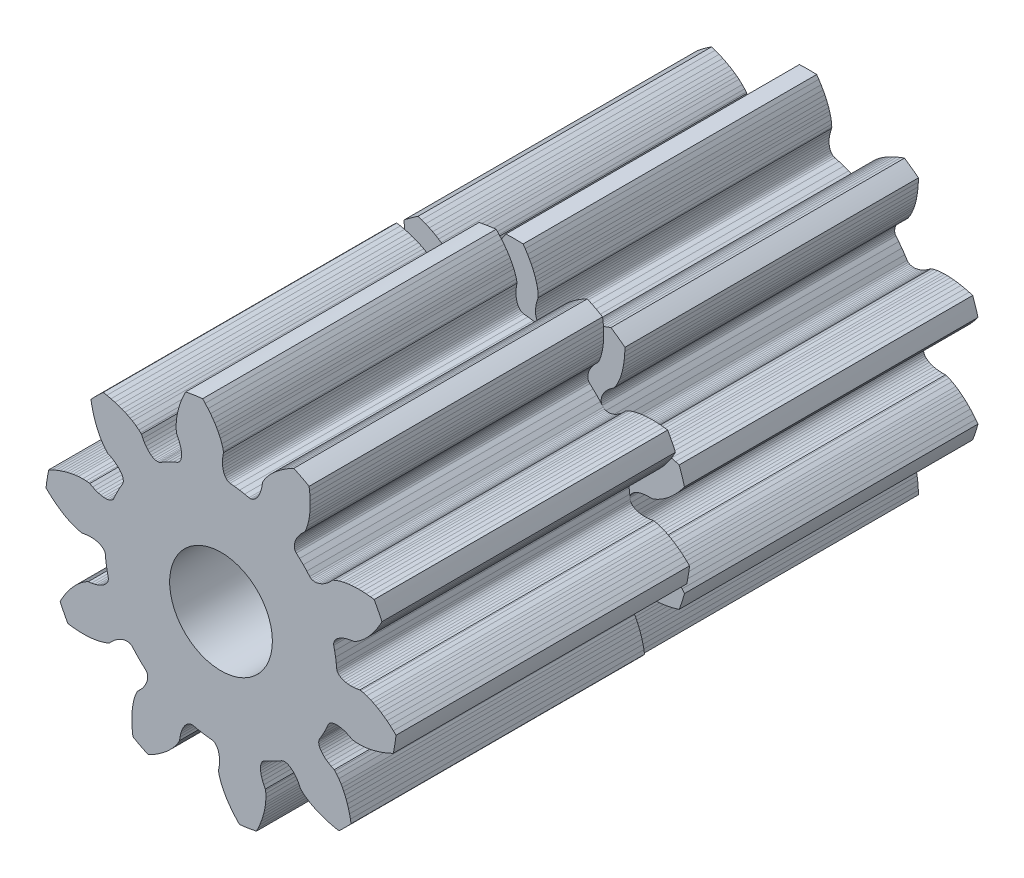
SolidWorks part; units mm, degrees
ref_plane "Front Plane" through (0, 0, 0) normal (0, 0, 1) x (1, 0, 0)
ref_plane "Top Plane" through (0, 0, 0) normal (0, 1, 0) x (1, 0, 0)
ref_plane "Right Plane" through (0, 0, 0) normal (1, 0, 0) x (0, 0, -1)
sketch "Sketch1" plane through (0, 0, 0) normal (0, 0, 1) x (1, 0, 0)
  line L0 (11.2428, -4.5485) -> (11.2517, -4.4039)
  line L1 (11.2517, -4.4039) -> (11.266, -4.2669)
  line L2 (11.266, -4.2669) -> (11.2847, -4.1393)
  line L3 (11.2847, -4.1393) -> (11.3071, -4.0209)
  line L4 (11.3071, -4.0209) -> (11.3325, -3.912)
  line L5 (11.3325, -3.912) -> (11.3608, -3.8103)
  line L6 (11.3608, -3.8103) -> (11.3897, -3.7211)
  line L7 (11.3897, -3.7211) -> (11.4208, -3.6371)
  line L8 (11.4208, -3.6371) -> (11.4807, -3.5016)
  line L9 (11.4807, -3.5016) -> (11.5377, -3.3971)
  line L10 (11.5377, -3.3971) -> (11.5845, -3.3262)
  line L11 (11.5845, -3.3262) -> (11.6076, -3.2964)
  line L12 (11.6076, -3.2964) -> (11.7007, -3.2317)
  line L13 (11.7007, -3.2317) -> (11.7827, -3.1653)
  line L14 (11.7827, -3.1653) -> (11.8533, -3.098)
  line L15 (11.8533, -3.098) -> (11.9128, -3.0308)
  line L16 (11.9128, -3.0308) -> (11.9612, -2.9643)
  line L17 (11.9612, -2.9643) -> (11.9989, -2.8995)
  line L18 (11.9989, -2.8995) -> (12.0259, -2.837)
  line L19 (12.0259, -2.837) -> (12.0426, -2.7776)
  line L20 (12.0426, -2.7776) -> (12.0493, -2.7222)
  line L21 (12.0493, -2.7222) -> (12.0463, -2.6714)
  line L22 (12.0463, -2.6714) -> (12.0342, -2.6259)
  line L23 (12.0342, -2.6259) -> (12.0067, -2.5776)
  line L24 (12.0067, -2.5776) -> (11.9109, -2.4617)
  line L25 (11.9109, -2.4617) -> (11.8044, -2.3217)
  line L26 (11.8044, -2.3217) -> (11.7041, -2.1772)
  line L27 (11.7041, -2.1772) -> (11.6236, -2.0503)
  line L28 (11.6236, -2.0503) -> (11.5861, -2.0092)
  line L29 (11.5861, -2.0092) -> (11.5466, -1.9836)
  line L30 (11.5466, -1.9836) -> (11.4992, -1.9651)
  line L31 (11.4992, -1.9651) -> (11.4444, -1.9543)
  line L32 (11.4444, -1.9543) -> (11.3828, -1.9518)
  line L33 (11.3828, -1.9518) -> (11.315, -1.9582)
  line L34 (11.315, -1.9582) -> (11.2417, -1.974)
  line L35 (11.2417, -1.974) -> (11.1635, -1.9995)
  line L36 (11.1635, -1.9995) -> (11.0812, -2.0353)
  line L37 (11.0812, -2.0353) -> (10.9954, -2.0817)
  line L38 (10.9954, -2.0817) -> (10.907, -2.1391)
  line L39 (10.907, -2.1391) -> (10.8166, -2.2077)
  line L40 (10.8166, -2.2077) -> (10.7811, -2.2204)
  line L41 (10.7811, -2.2204) -> (10.6992, -2.243)
  line L42 (10.6992, -2.243) -> (10.5823, -2.2649)
  line L43 (10.5823, -2.2649) -> (10.4348, -2.2801)
  line L44 (10.4348, -2.2801) -> (10.3453, -2.2837)
  line L45 (10.3453, -2.2837) -> (10.2516, -2.2836)
  line L46 (10.2516, -2.2836) -> (10.1461, -2.2791)
  line L47 (10.1461, -2.2791) -> (10.0348, -2.2696)
  line L48 (10.0348, -2.2696) -> (9.9151, -2.2543)
  line L49 (9.9151, -2.2543) -> (9.7881, -2.2327)
  line L50 (9.7881, -2.2327) -> (9.6533, -2.2039)
  line L51 (9.6533, -2.2039) -> (9.5131, -2.1677)
  line L52 (9.5131, -2.1677) -> (9.3912, -2.1311)
  line L53 (9.2098, -1.5726) -> (9.2868, -1.4714)
  line L54 (9.2868, -1.4714) -> (9.379, -1.3597)
  line L55 (9.379, -1.3597) -> (9.4711, -1.2572)
  line L56 (9.4711, -1.2572) -> (9.5612, -1.165)
  line L57 (9.5612, -1.165) -> (9.649, -1.0823)
  line L58 (9.649, -1.0823) -> (9.7335, -1.0092)
  line L59 (9.7335, -1.0092) -> (9.8162, -0.9435)
  line L60 (9.8162, -0.9435) -> (9.8919, -0.8883)
  line L61 (9.8919, -0.8883) -> (9.9665, -0.8387)
  line L62 (9.9665, -0.8387) -> (10.0947, -0.7642)
  line L63 (10.0947, -0.7642) -> (10.2021, -0.7133)
  line L64 (10.2021, -0.7133) -> (10.2817, -0.6834)
  line L65 (10.2817, -0.6834) -> (10.3179, -0.6728)
  line L66 (10.3179, -0.6728) -> (10.4313, -0.6752)
  line L67 (10.4313, -0.6752) -> (10.5366, -0.6696)
  line L68 (10.5366, -0.6696) -> (10.6333, -0.6568)
  line L69 (10.6333, -0.6568) -> (10.7209, -0.6373)
  line L70 (10.7209, -0.6373) -> (10.7992, -0.612)
  line L71 (10.7992, -0.612) -> (10.8678, -0.5817)
  line L72 (10.8678, -0.5817) -> (10.9263, -0.547)
  line L73 (10.9263, -0.547) -> (10.9747, -0.5088)
  line L74 (10.9747, -0.5088) -> (11.0127, -0.4679)
  line L75 (11.0127, -0.4679) -> (11.0402, -0.4251)
  line L76 (11.0402, -0.4251) -> (11.0571, -0.3811)
  line L77 (11.0571, -0.3811) -> (11.0633, -0.3259)
  line L78 (11.0633, -0.3259) -> (11.0539, -0.1759)
  line L79 (11.0539, -0.1759) -> (11.05, 0)
  line L80 (11.05, 0) -> (11.0539, 0.1759)
  line L81 (11.0539, 0.1759) -> (11.0633, 0.3259)
  line L82 (11.0633, 0.3259) -> (11.0571, 0.3812)
  line L83 (11.0571, 0.3812) -> (11.0402, 0.4251)
  line L84 (11.0402, 0.4251) -> (11.0127, 0.468)
  line L85 (11.0127, 0.468) -> (10.9747, 0.5089)
  line L86 (10.9747, 0.5089) -> (10.9263, 0.5471)
  line L87 (10.9263, 0.5471) -> (10.8678, 0.5817)
  line L88 (10.8678, 0.5817) -> (10.7992, 0.6121)
  line L89 (10.7992, 0.6121) -> (10.7209, 0.6374)
  line L90 (10.7209, 0.6374) -> (10.6333, 0.6568)
  line L91 (10.6333, 0.6568) -> (10.5366, 0.6697)
  line L92 (10.5366, 0.6697) -> (10.4313, 0.6753)
  line L93 (10.4313, 0.6753) -> (10.3179, 0.6729)
  line L94 (10.3179, 0.6729) -> (10.2817, 0.6834)
  line L95 (10.2817, 0.6834) -> (10.2021, 0.7133)
  line L96 (10.2021, 0.7133) -> (10.0947, 0.7643)
  line L97 (10.0947, 0.7643) -> (9.9665, 0.8387)
  line L98 (9.9665, 0.8387) -> (9.8919, 0.8884)
  line L99 (9.8919, 0.8884) -> (9.8162, 0.9436)
  line L100 (9.8162, 0.9436) -> (9.7335, 1.0093)
  line L101 (9.7335, 1.0093) -> (9.649, 1.0824)
  line L102 (9.649, 1.0824) -> (9.5612, 1.165)
  line L103 (9.5612, 1.165) -> (9.4711, 1.2572)
  line L104 (9.4711, 1.2572) -> (9.379, 1.3597)
  line L105 (9.379, 1.3597) -> (9.2868, 1.4714)
  line L106 (9.2868, 1.4714) -> (9.2098, 1.5727)
  line L107 (9.3912, 2.1311) -> (9.5131, 2.1677)
  line L108 (9.5131, 2.1677) -> (9.6533, 2.2039)
  line L109 (9.6533, 2.2039) -> (9.788, 2.2327)
  line L110 (9.788, 2.2327) -> (9.9151, 2.2544)
  line L111 (9.9151, 2.2544) -> (10.0347, 2.2696)
  line L112 (10.0347, 2.2696) -> (10.1461, 2.2791)
  line L113 (10.1461, 2.2791) -> (10.2516, 2.2836)
  line L114 (10.2516, 2.2836) -> (10.3453, 2.2837)
  line L115 (10.3453, 2.2837) -> (10.4348, 2.2801)
  line L116 (10.4348, 2.2801) -> (10.5823, 2.265)
  line L117 (10.5823, 2.265) -> (10.6992, 2.2431)
  line L118 (10.6992, 2.2431) -> (10.7811, 2.2205)
  line L119 (10.7811, 2.2205) -> (10.8166, 2.2078)
  line L120 (10.8166, 2.2078) -> (10.9069, 2.1391)
  line L121 (10.9069, 2.1391) -> (10.9954, 2.0818)
  line L122 (10.9954, 2.0818) -> (11.0812, 2.0353)
  line L123 (11.0812, 2.0353) -> (11.1635, 1.9995)
  line L124 (11.1635, 1.9995) -> (11.2417, 1.974)
  line L125 (11.2417, 1.974) -> (11.315, 1.9583)
  line L126 (11.315, 1.9583) -> (11.3828, 1.9519)
  line L127 (11.3828, 1.9519) -> (11.4444, 1.9543)
  line L128 (11.4444, 1.9543) -> (11.4991, 1.9651)
  line L129 (11.4991, 1.9651) -> (11.5465, 1.9836)
  line L130 (11.5465, 1.9836) -> (11.586, 2.0092)
  line L131 (11.586, 2.0092) -> (11.6235, 2.0503)
  line L132 (11.6235, 2.0503) -> (11.7041, 2.1772)
  line L133 (11.7041, 2.1772) -> (11.8043, 2.3218)
  line L134 (11.8043, 2.3218) -> (11.9109, 2.4618)
  line L135 (11.9109, 2.4618) -> (12.0067, 2.5776)
  line L136 (12.0067, 2.5776) -> (12.0341, 2.626)
  line L137 (12.0341, 2.626) -> (12.0463, 2.6715)
  line L138 (12.0463, 2.6715) -> (12.0492, 2.7223)
  line L139 (12.0492, 2.7223) -> (12.0426, 2.7777)
  line L140 (12.0426, 2.7777) -> (12.0259, 2.837)
  line L141 (12.0259, 2.837) -> (11.9988, 2.8995)
  line L142 (11.9988, 2.8995) -> (11.9612, 2.9643)
  line L143 (11.9612, 2.9643) -> (11.9128, 3.0308)
  line L144 (11.9128, 3.0308) -> (11.8533, 3.0981)
  line L145 (11.8533, 3.0981) -> (11.7826, 3.1653)
  line L146 (11.7826, 3.1653) -> (11.7007, 3.2317)
  line L147 (11.7007, 3.2317) -> (11.6075, 3.2964)
  line L148 (11.6075, 3.2964) -> (11.5845, 3.3262)
  line L149 (11.5845, 3.3262) -> (11.5377, 3.3972)
  line L150 (11.5377, 3.3972) -> (11.4807, 3.5016)
  line L151 (11.4807, 3.5016) -> (11.4208, 3.6372)
  line L152 (11.4208, 3.6372) -> (11.3896, 3.7212)
  line L153 (11.3896, 3.7212) -> (11.3608, 3.8103)
  line L154 (11.3608, 3.8103) -> (11.3325, 3.9121)
  line L155 (11.3325, 3.9121) -> (11.3071, 4.0209)
  line L156 (11.3071, 4.0209) -> (11.2846, 4.1394)
  line L157 (11.2846, 4.1394) -> (11.2659, 4.2669)
  line L158 (11.2659, 4.2669) -> (11.2517, 4.404)
  line L159 (11.2517, 4.404) -> (11.2428, 4.5485)
  line L160 (11.2428, 4.5485) -> (11.2399, 4.6757)
  line L161 (11.715, 5.0209) -> (11.8351, 4.9789)
  line L162 (11.8351, 4.9789) -> (11.9698, 4.9257)
  line L163 (11.9698, 4.9257) -> (12.0958, 4.8698)
  line L164 (12.0958, 4.8698) -> (12.2113, 4.8127)
  line L165 (12.2113, 4.8127) -> (12.3171, 4.7547)
  line L166 (12.3171, 4.7547) -> (12.4127, 4.6969)
  line L167 (12.4127, 4.6969) -> (12.5007, 4.6385)
  line L168 (12.5007, 4.6385) -> (12.5766, 4.5836)
  line L169 (12.5766, 4.5836) -> (12.6469, 4.528)
  line L170 (12.6469, 4.528) -> (12.7573, 4.4291)
  line L171 (12.7573, 4.4291) -> (12.839, 4.3427)
  line L172 (12.839, 4.3427) -> (12.892, 4.2762)
  line L173 (12.892, 4.2762) -> (12.9132, 4.2451)
  line L174 (12.9132, 4.2451) -> (12.946, 4.1364)
  line L175 (12.946, 4.1364) -> (12.9838, 4.038)
  line L176 (12.9838, 4.038) -> (13.0259, 3.9501)
  line L177 (13.0259, 3.9501) -> (13.0715, 3.8727)
  line L178 (13.0715, 3.8727) -> (13.1197, 3.8061)
  line L179 (13.1197, 3.8061) -> (13.1698, 3.7503)
  line L180 (13.1698, 3.7503) -> (13.2209, 3.7053)
  line L181 (13.2209, 3.7053) -> (13.2721, 3.671)
  line L182 (13.2721, 3.671) -> (13.3228, 3.6476)
  line L183 (13.3228, 3.6476) -> (13.372, 3.6347)
  line L184 (13.372, 3.6347) -> (13.419, 3.6322)
  line L185 (13.419, 3.6322) -> (13.4735, 3.6434)
  line L186 (13.4735, 3.6434) -> (13.6133, 3.6987)
  line L187 (13.6133, 3.6987) -> (13.7794, 3.7567)
  line L188 (13.7794, 3.7567) -> (13.9478, 3.8074)
  line L189 (13.9478, 3.8074) -> (14.0934, 3.8448)
  line L190 (14.0934, 3.8448) -> (14.1441, 3.8678)
  line L191 (14.1441, 3.8678) -> (14.1806, 3.8974)
  line L192 (14.1806, 3.8974) -> (14.2129, 3.9368)
  line L193 (14.2129, 3.9368) -> (14.2401, 3.9855)
  line L194 (14.2401, 3.9855) -> (14.2614, 4.0434)
  line L195 (14.2614, 4.0434) -> (14.2763, 4.1098)
  line L196 (14.2763, 4.1098) -> (14.284, 4.1844)
  line L197 (14.284, 4.1844) -> (14.2838, 4.2666)
  line L198 (14.2838, 4.2666) -> (14.2752, 4.356)
  line L199 (14.2752, 4.356) -> (14.2576, 4.4519)
  line L200 (14.2576, 4.4519) -> (14.2304, 4.5538)
  line L201 (14.2304, 4.5538) -> (14.193, 4.6609)
  line L202 (14.193, 4.6609) -> (14.1919, 4.6986)
  line L203 (14.1919, 4.6986) -> (14.1957, 4.7835)
  line L204 (14.1957, 4.7835) -> (14.211, 4.9014)
  line L205 (14.211, 4.9014) -> (14.2422, 5.0463)
  line L206 (14.2422, 5.0463) -> (14.2664, 5.1326)
  line L207 (14.2664, 5.1326) -> (14.2955, 5.2217)
  line L208 (14.2955, 5.2217) -> (14.3324, 5.3207)
  line L209 (14.3324, 5.3207) -> (14.3758, 5.4236)
  line L210 (14.3758, 5.4236) -> (14.4273, 5.5327)
  line L211 (14.4273, 5.5327) -> (14.4871, 5.6468)
  line L212 (14.4871, 5.6468) -> (14.5562, 5.7661)
  line L213 (14.5562, 5.7661) -> (14.6339, 5.8883)
  line L214 (14.6339, 5.8883) -> (14.7064, 5.9928)
  line L215 (15.2936, 5.9928) -> (15.3661, 5.8883)
  line L216 (15.3661, 5.8883) -> (15.4438, 5.7661)
  line L217 (15.4438, 5.7661) -> (15.5128, 5.6468)
  line L218 (15.5128, 5.6468) -> (15.5727, 5.5327)
  line L219 (15.5727, 5.5327) -> (15.6242, 5.4236)
  line L220 (15.6242, 5.4236) -> (15.6676, 5.3207)
  line L221 (15.6676, 5.3207) -> (15.7045, 5.2217)
  line L222 (15.7045, 5.2217) -> (15.7336, 5.1326)
  line L223 (15.7336, 5.1326) -> (15.7578, 5.0464)
  line L224 (15.7578, 5.0464) -> (15.7889, 4.9014)
  line L225 (15.7889, 4.9014) -> (15.8042, 4.7835)
  line L226 (15.8042, 4.7835) -> (15.8081, 4.6986)
  line L227 (15.8081, 4.6986) -> (15.8069, 4.6609)
  line L228 (15.8069, 4.6609) -> (15.7696, 4.5538)
  line L229 (15.7696, 4.5538) -> (15.7424, 4.4519)
  line L230 (15.7424, 4.4519) -> (15.7247, 4.356)
  line L231 (15.7247, 4.356) -> (15.7161, 4.2666)
  line L232 (15.7161, 4.2666) -> (15.716, 4.1844)
  line L233 (15.716, 4.1844) -> (15.7237, 4.1098)
  line L234 (15.7237, 4.1098) -> (15.7385, 4.0434)
  line L235 (15.7385, 4.0434) -> (15.7599, 3.9855)
  line L236 (15.7599, 3.9855) -> (15.7871, 3.9368)
  line L237 (15.7871, 3.9368) -> (15.8193, 3.8974)
  line L238 (15.8193, 3.8974) -> (15.8559, 3.8678)
  line L239 (15.8559, 3.8678) -> (15.9065, 3.8448)
  line L240 (15.9065, 3.8448) -> (16.0521, 3.8074)
  line L241 (16.0521, 3.8074) -> (16.2206, 3.7567)
  line L242 (16.2206, 3.7567) -> (16.3867, 3.6987)
  line L243 (16.3867, 3.6987) -> (16.5264, 3.6434)
  line L244 (16.5264, 3.6434) -> (16.5809, 3.6322)
  line L245 (16.5809, 3.6322) -> (16.6279, 3.6347)
  line L246 (16.6279, 3.6347) -> (16.6772, 3.6476)
  line L247 (16.6772, 3.6476) -> (16.7278, 3.6711)
  line L248 (16.7278, 3.6711) -> (16.7791, 3.7053)
  line L249 (16.7791, 3.7053) -> (16.8301, 3.7503)
  line L250 (16.8301, 3.7503) -> (16.8802, 3.8061)
  line L251 (16.8802, 3.8061) -> (16.9284, 3.8727)
  line L252 (16.9284, 3.8727) -> (16.974, 3.9501)
  line L253 (16.974, 3.9501) -> (17.0161, 4.038)
  line L254 (17.0161, 4.038) -> (17.054, 4.1365)
  line L255 (17.054, 4.1365) -> (17.0867, 4.2451)
  line L256 (17.0867, 4.2451) -> (17.108, 4.2762)
  line L257 (17.108, 4.2762) -> (17.161, 4.3427)
  line L258 (17.161, 4.3427) -> (17.2427, 4.4291)
  line L259 (17.2427, 4.4291) -> (17.3531, 4.528)
  line L260 (17.3531, 4.528) -> (17.4233, 4.5836)
  line L261 (17.4233, 4.5836) -> (17.4992, 4.6385)
  line L262 (17.4992, 4.6385) -> (17.5873, 4.6969)
  line L263 (17.5873, 4.6969) -> (17.6829, 4.7547)
  line L264 (17.6829, 4.7547) -> (17.7886, 4.8127)
  line L265 (17.7886, 4.8127) -> (17.9042, 4.8699)
  line L266 (17.9042, 4.8699) -> (18.0301, 4.9258)
  line L267 (18.0301, 4.9258) -> (18.1648, 4.9789)
  line L268 (18.1648, 4.9789) -> (18.2849, 5.0209)
  line L269 (18.76, 4.6758) -> (18.7572, 4.5486)
  line L270 (18.7572, 4.5486) -> (18.7483, 4.404)
  line L271 (18.7483, 4.404) -> (18.734, 4.2669)
  line L272 (18.734, 4.2669) -> (18.7153, 4.1394)
  line L273 (18.7153, 4.1394) -> (18.6928, 4.0209)
  line L274 (18.6928, 4.0209) -> (18.6675, 3.9121)
  line L275 (18.6675, 3.9121) -> (18.6392, 3.8103)
  line L276 (18.6392, 3.8103) -> (18.6103, 3.7212)
  line L277 (18.6103, 3.7212) -> (18.5792, 3.6372)
  line L278 (18.5792, 3.6372) -> (18.5192, 3.5016)
  line L279 (18.5192, 3.5016) -> (18.4623, 3.3972)
  line L280 (18.4623, 3.3972) -> (18.4155, 3.3263)
  line L281 (18.4155, 3.3263) -> (18.3924, 3.2965)
  line L282 (18.3924, 3.2965) -> (18.2992, 3.2317)
  line L283 (18.2992, 3.2317) -> (18.2173, 3.1653)
  line L284 (18.2173, 3.1653) -> (18.1467, 3.0981)
  line L285 (18.1467, 3.0981) -> (18.0872, 3.0308)
  line L286 (18.0872, 3.0308) -> (18.0387, 2.9644)
  line L287 (18.0387, 2.9644) -> (18.0011, 2.8995)
  line L288 (18.0011, 2.8995) -> (17.9741, 2.837)
  line L289 (17.9741, 2.837) -> (17.9574, 2.7777)
  line L290 (17.9574, 2.7777) -> (17.9507, 2.7223)
  line L291 (17.9507, 2.7223) -> (17.9537, 2.6715)
  line L292 (17.9537, 2.6715) -> (17.9658, 2.626)
  line L293 (17.9658, 2.626) -> (17.9933, 2.5777)
  line L294 (17.9933, 2.5777) -> (18.0891, 2.4618)
  line L295 (18.0891, 2.4618) -> (18.1956, 2.3218)
  line L296 (18.1956, 2.3218) -> (18.2959, 2.1772)
  line L297 (18.2959, 2.1772) -> (18.3764, 2.0503)
  line L298 (18.3764, 2.0503) -> (18.4139, 2.0093)
  line L299 (18.4139, 2.0093) -> (18.4534, 1.9836)
  line L300 (18.4534, 1.9836) -> (18.5008, 1.9651)
  line L301 (18.5008, 1.9651) -> (18.5556, 1.9544)
  line L302 (18.5556, 1.9544) -> (18.6172, 1.9519)
  line L303 (18.6172, 1.9519) -> (18.6849, 1.9583)
  line L304 (18.6849, 1.9583) -> (18.7583, 1.974)
  line L305 (18.7583, 1.974) -> (18.8364, 1.9996)
  line L306 (18.8364, 1.9996) -> (18.9188, 2.0354)
  line L307 (18.9188, 2.0354) -> (19.0046, 2.0818)
  line L308 (19.0046, 2.0818) -> (19.093, 2.1392)
  line L309 (19.093, 2.1392) -> (19.1834, 2.2078)
  line L310 (19.1834, 2.2078) -> (19.2188, 2.2205)
  line L311 (19.2188, 2.2205) -> (19.3008, 2.2431)
  line L312 (19.3008, 2.2431) -> (19.4177, 2.265)
  line L313 (19.4177, 2.265) -> (19.5651, 2.2801)
  line L314 (19.5651, 2.2801) -> (19.6547, 2.2838)
  line L315 (19.6547, 2.2838) -> (19.7484, 2.2837)
  line L316 (19.7484, 2.2837) -> (19.8539, 2.2791)
  line L317 (19.8539, 2.2791) -> (19.9652, 2.2696)
  line L318 (19.9652, 2.2696) -> (20.0848, 2.2544)
  line L319 (20.0848, 2.2544) -> (20.2119, 2.2328)
  line L320 (20.2119, 2.2328) -> (20.3467, 2.204)
  line L321 (20.3467, 2.204) -> (20.4869, 2.1678)
  line L322 (20.4869, 2.1678) -> (20.6088, 2.1312)
  line L323 (20.7902, 1.5727) -> (20.7132, 1.4714)
  line L324 (20.7132, 1.4714) -> (20.621, 1.3598)
  line L325 (20.621, 1.3598) -> (20.5289, 1.2572)
  line L326 (20.5289, 1.2572) -> (20.4388, 1.165)
  line L327 (20.4388, 1.165) -> (20.351, 1.0824)
  line L328 (20.351, 1.0824) -> (20.2665, 1.0093)
  line L329 (20.2665, 1.0093) -> (20.1838, 0.9436)
  line L330 (20.1838, 0.9436) -> (20.108, 0.8884)
  line L331 (20.108, 0.8884) -> (20.0335, 0.8388)
  line L332 (20.0335, 0.8388) -> (19.9053, 0.7643)
  line L333 (19.9053, 0.7643) -> (19.7979, 0.7133)
  line L334 (19.7979, 0.7133) -> (19.7183, 0.6834)
  line L335 (19.7183, 0.6834) -> (19.6821, 0.6729)
  line L336 (19.6821, 0.6729) -> (19.5687, 0.6753)
  line L337 (19.5687, 0.6753) -> (19.4634, 0.6697)
  line L338 (19.4634, 0.6697) -> (19.3667, 0.6568)
  line L339 (19.3667, 0.6568) -> (19.279, 0.6374)
  line L340 (19.279, 0.6374) -> (19.2008, 0.6121)
  line L341 (19.2008, 0.6121) -> (19.1322, 0.5818)
  line L342 (19.1322, 0.5818) -> (19.0736, 0.5471)
  line L343 (19.0736, 0.5471) -> (19.0253, 0.5089)
  line L344 (19.0253, 0.5089) -> (18.9873, 0.468)
  line L345 (18.9873, 0.468) -> (18.9598, 0.4252)
  line L346 (18.9598, 0.4252) -> (18.9429, 0.3812)
  line L347 (18.9429, 0.3812) -> (18.9367, 0.3259)
  line L348 (18.9367, 0.3259) -> (18.9461, 0.1759)
  line L349 (18.9461, 0.1759) -> (18.95, 0)
  line L350 (18.95, 0) -> (18.9461, -0.1758)
  line L351 (18.9461, -0.1758) -> (18.9367, -0.3259)
  line L352 (18.9367, -0.3259) -> (18.9429, -0.3811)
  line L353 (18.9429, -0.3811) -> (18.9598, -0.4251)
  line L354 (18.9598, -0.4251) -> (18.9873, -0.4679)
  line L355 (18.9873, -0.4679) -> (19.0253, -0.5088)
  line L356 (19.0253, -0.5088) -> (19.0736, -0.547)
  line L357 (19.0736, -0.547) -> (19.1322, -0.5817)
  line L358 (19.1322, -0.5817) -> (19.2008, -0.612)
  line L359 (19.2008, -0.612) -> (19.279, -0.6373)
  line L360 (19.279, -0.6373) -> (19.3667, -0.6567)
  line L361 (19.3667, -0.6567) -> (19.4634, -0.6696)
  line L362 (19.4634, -0.6696) -> (19.5687, -0.6752)
  line L363 (19.5687, -0.6752) -> (19.6821, -0.6728)
  line L364 (19.6821, -0.6728) -> (19.7183, -0.6834)
  line L365 (19.7183, -0.6834) -> (19.7979, -0.7132)
  line L366 (19.7979, -0.7132) -> (19.9053, -0.7642)
  line L367 (19.9053, -0.7642) -> (20.0335, -0.8387)
  line L368 (20.0335, -0.8387) -> (20.108, -0.8883)
  line L369 (20.108, -0.8883) -> (20.1838, -0.9435)
  line L370 (20.1838, -0.9435) -> (20.2665, -1.0092)
  line L371 (20.2665, -1.0092) -> (20.351, -1.0823)
  line L372 (20.351, -1.0823) -> (20.4388, -1.1649)
  line L373 (20.4388, -1.1649) -> (20.5289, -1.2571)
  line L374 (20.5289, -1.2571) -> (20.621, -1.3597)
  line L375 (20.621, -1.3597) -> (20.7132, -1.4714)
  line L376 (20.7132, -1.4714) -> (20.7902, -1.5726)
  line L377 (20.6088, -2.131) -> (20.4869, -2.1677)
  line L378 (20.4869, -2.1677) -> (20.3467, -2.2039)
  line L379 (20.3467, -2.2039) -> (20.2119, -2.2327)
  line L380 (20.2119, -2.2327) -> (20.0849, -2.2543)
  line L381 (20.0849, -2.2543) -> (19.9652, -2.2695)
  line L382 (19.9652, -2.2695) -> (19.8539, -2.279)
  line L383 (19.8539, -2.279) -> (19.7484, -2.2836)
  line L384 (19.7484, -2.2836) -> (19.6547, -2.2837)
  line L385 (19.6547, -2.2837) -> (19.5652, -2.28)
  line L386 (19.5652, -2.28) -> (19.4177, -2.2649)
  line L387 (19.4177, -2.2649) -> (19.3008, -2.243)
  line L388 (19.3008, -2.243) -> (19.2189, -2.2204)
  line L389 (19.2189, -2.2204) -> (19.1834, -2.2077)
  line L390 (19.1834, -2.2077) -> (19.093, -2.1391)
  line L391 (19.093, -2.1391) -> (19.0046, -2.0817)
  line L392 (19.0046, -2.0817) -> (18.9188, -2.0353)
  line L393 (18.9188, -2.0353) -> (18.8365, -1.9995)
  line L394 (18.8365, -1.9995) -> (18.7583, -1.9739)
  line L395 (18.7583, -1.9739) -> (18.685, -1.9582)
  line L396 (18.685, -1.9582) -> (18.6172, -1.9518)
  line L397 (18.6172, -1.9518) -> (18.5556, -1.9543)
  line L398 (18.5556, -1.9543) -> (18.5008, -1.965)
  line L399 (18.5008, -1.965) -> (18.4534, -1.9835)
  line L400 (18.4534, -1.9835) -> (18.4139, -2.0092)
  line L401 (18.4139, -2.0092) -> (18.3764, -2.0502)
  line L402 (18.3764, -2.0502) -> (18.2959, -2.1771)
  line L403 (18.2959, -2.1771) -> (18.1956, -2.3217)
  line L404 (18.1956, -2.3217) -> (18.0891, -2.4617)
  line L405 (18.0891, -2.4617) -> (17.9933, -2.5776)
  line L406 (17.9933, -2.5776) -> (17.9658, -2.6259)
  line L407 (17.9658, -2.6259) -> (17.9537, -2.6714)
  line L408 (17.9537, -2.6714) -> (17.9507, -2.7222)
  line L409 (17.9507, -2.7222) -> (17.9574, -2.7776)
  line L410 (17.9574, -2.7776) -> (17.9741, -2.8369)
  line L411 (17.9741, -2.8369) -> (18.0011, -2.8994)
  line L412 (18.0011, -2.8994) -> (18.0387, -2.9643)
  line L413 (18.0387, -2.9643) -> (18.0872, -3.0307)
  line L414 (18.0872, -3.0307) -> (18.1467, -3.098)
  line L415 (18.1467, -3.098) -> (18.2173, -3.1652)
  line L416 (18.2173, -3.1652) -> (18.2992, -3.2316)
  line L417 (18.2992, -3.2316) -> (18.3924, -3.2964)
  line L418 (18.3924, -3.2964) -> (18.4155, -3.3262)
  line L419 (18.4155, -3.3262) -> (18.4623, -3.3971)
  line L420 (18.4623, -3.3971) -> (18.5193, -3.5015)
  line L421 (18.5193, -3.5015) -> (18.5792, -3.6371)
  line L422 (18.5792, -3.6371) -> (18.6103, -3.7211)
  line L423 (18.6103, -3.7211) -> (18.6392, -3.8102)
  line L424 (18.6392, -3.8102) -> (18.6675, -3.912)
  line L425 (18.6675, -3.912) -> (18.6929, -4.0208)
  line L426 (18.6929, -4.0208) -> (18.7153, -4.1393)
  line L427 (18.7153, -4.1393) -> (18.734, -4.2668)
  line L428 (18.734, -4.2668) -> (18.7483, -4.4039)
  line L429 (18.7483, -4.4039) -> (18.7572, -4.5484)
  line L430 (18.7572, -4.5484) -> (18.76, -4.6757)
  line L431 (18.285, -5.0208) -> (18.1648, -4.9788)
  line L432 (18.1648, -4.9788) -> (18.0301, -4.9257)
  line L433 (18.0301, -4.9257) -> (17.9042, -4.8698)
  line L434 (17.9042, -4.8698) -> (17.7886, -4.8126)
  line L435 (17.7886, -4.8126) -> (17.6829, -4.7546)
  line L436 (17.6829, -4.7546) -> (17.5873, -4.6968)
  line L437 (17.5873, -4.6968) -> (17.4992, -4.6385)
  line L438 (17.4992, -4.6385) -> (17.4234, -4.5835)
  line L439 (17.4234, -4.5835) -> (17.3531, -4.5279)
  line L440 (17.3531, -4.5279) -> (17.2427, -4.429)
  line L441 (17.2427, -4.429) -> (17.161, -4.3426)
  line L442 (17.161, -4.3426) -> (17.108, -4.2761)
  line L443 (17.108, -4.2761) -> (17.0868, -4.245)
  line L444 (17.0868, -4.245) -> (17.054, -4.1364)
  line L445 (17.054, -4.1364) -> (17.0161, -4.038)
  line L446 (17.0161, -4.038) -> (16.974, -3.95)
  line L447 (16.974, -3.95) -> (16.9284, -3.8726)
  line L448 (16.9284, -3.8726) -> (16.8802, -3.806)
  line L449 (16.8802, -3.806) -> (16.8302, -3.7502)
  line L450 (16.8302, -3.7502) -> (16.7791, -3.7052)
  line L451 (16.7791, -3.7052) -> (16.7278, -3.671)
  line L452 (16.7278, -3.671) -> (16.6772, -3.6475)
  line L453 (16.6772, -3.6475) -> (16.6279, -3.6346)
  line L454 (16.6279, -3.6346) -> (16.5809, -3.6321)
  line L455 (16.5809, -3.6321) -> (16.5265, -3.6433)
  line L456 (16.5265, -3.6433) -> (16.3867, -3.6986)
  line L457 (16.3867, -3.6986) -> (16.2206, -3.7567)
  line L458 (16.2206, -3.7567) -> (16.0521, -3.8073)
  line L459 (16.0521, -3.8073) -> (15.9066, -3.8447)
  line L460 (15.9066, -3.8447) -> (15.8559, -3.8677)
  line L461 (15.8559, -3.8677) -> (15.8193, -3.8973)
  line L462 (15.8193, -3.8973) -> (15.7871, -3.9367)
  line L463 (15.7871, -3.9367) -> (15.7599, -3.9855)
  line L464 (15.7599, -3.9855) -> (15.7385, -4.0433)
  line L465 (15.7385, -4.0433) -> (15.7237, -4.1097)
  line L466 (15.7237, -4.1097) -> (15.716, -4.1843)
  line L467 (15.716, -4.1843) -> (15.7161, -4.2665)
  line L468 (15.7161, -4.2665) -> (15.7247, -4.3559)
  line L469 (15.7247, -4.3559) -> (15.7424, -4.4518)
  line L470 (15.7424, -4.4518) -> (15.7696, -4.5537)
  line L471 (15.7696, -4.5537) -> (15.8069, -4.6609)
  line L472 (15.8069, -4.6609) -> (15.8081, -4.6985)
  line L473 (15.8081, -4.6985) -> (15.8042, -4.7834)
  line L474 (15.8042, -4.7834) -> (15.789, -4.9014)
  line L475 (15.789, -4.9014) -> (15.7578, -5.0463)
  line L476 (15.7578, -5.0463) -> (15.7336, -5.1325)
  line L477 (15.7336, -5.1325) -> (15.7045, -5.2216)
  line L478 (15.7045, -5.2216) -> (15.6676, -5.3206)
  line L479 (15.6676, -5.3206) -> (15.6242, -5.4235)
  line L480 (15.6242, -5.4235) -> (15.5727, -5.5326)
  line L481 (15.5727, -5.5326) -> (15.5129, -5.6468)
  line L482 (15.5129, -5.6468) -> (15.4438, -5.766)
  line L483 (15.4438, -5.766) -> (15.3661, -5.8882)
  line L484 (15.3661, -5.8882) -> (15.2936, -5.9928)
  line L485 (14.7064, -5.9928) -> (14.6339, -5.8882)
  line L486 (14.6339, -5.8882) -> (14.5561, -5.766)
  line L487 (14.5561, -5.766) -> (14.4871, -5.6468)
  line L488 (14.4871, -5.6468) -> (14.4272, -5.5326)
  line L489 (14.4272, -5.5326) -> (14.3758, -5.4235)
  line L490 (14.3758, -5.4235) -> (14.3324, -5.3206)
  line L491 (14.3324, -5.3206) -> (14.2954, -5.2216)
  line L492 (14.2954, -5.2216) -> (14.2664, -5.1325)
  line L493 (14.2664, -5.1325) -> (14.2422, -5.0463)
  line L494 (14.2422, -5.0463) -> (14.211, -4.9014)
  line L495 (14.211, -4.9014) -> (14.1957, -4.7834)
  line L496 (14.1957, -4.7834) -> (14.1919, -4.6985)
  line L497 (14.1919, -4.6985) -> (14.193, -4.6608)
  line L498 (14.193, -4.6608) -> (14.2304, -4.5537)
  line L499 (14.2304, -4.5537) -> (14.2576, -4.4518)
  line L500 (14.2576, -4.4518) -> (14.2752, -4.3559)
  line L501 (14.2752, -4.3559) -> (14.2838, -4.2665)
  line L502 (14.2838, -4.2665) -> (14.284, -4.1843)
  line L503 (14.284, -4.1843) -> (14.2763, -4.1097)
  line L504 (14.2763, -4.1097) -> (14.2614, -4.0433)
  line L505 (14.2614, -4.0433) -> (14.24, -3.9855)
  line L506 (14.24, -3.9855) -> (14.2129, -3.9367)
  line L507 (14.2129, -3.9367) -> (14.1806, -3.8973)
  line L508 (14.1806, -3.8973) -> (14.144, -3.8677)
  line L509 (14.144, -3.8677) -> (14.0934, -3.8447)
  line L510 (14.0934, -3.8447) -> (13.9478, -3.8073)
  line L511 (13.9478, -3.8073) -> (13.7793, -3.7567)
  line L512 (13.7793, -3.7567) -> (13.6133, -3.6986)
  line L513 (13.6133, -3.6986) -> (13.4735, -3.6433)
  line L514 (13.4735, -3.6433) -> (13.419, -3.6321)
  line L515 (13.419, -3.6321) -> (13.372, -3.6346)
  line L516 (13.372, -3.6346) -> (13.3228, -3.6475)
  line L517 (13.3228, -3.6475) -> (13.2721, -3.671)
  line L518 (13.2721, -3.671) -> (13.2209, -3.7052)
  line L519 (13.2209, -3.7052) -> (13.1698, -3.7502)
  line L520 (13.1698, -3.7502) -> (13.1197, -3.806)
  line L521 (13.1197, -3.806) -> (13.0715, -3.8726)
  line L522 (13.0715, -3.8726) -> (13.0259, -3.95)
  line L523 (13.0259, -3.95) -> (12.9838, -4.038)
  line L524 (12.9838, -4.038) -> (12.946, -4.1364)
  line L525 (12.946, -4.1364) -> (12.9132, -4.245)
  line L526 (12.9132, -4.245) -> (12.892, -4.2761)
  line L527 (12.892, -4.2761) -> (12.839, -4.3426)
  line L528 (12.839, -4.3426) -> (12.7573, -4.429)
  line L529 (12.7573, -4.429) -> (12.6469, -4.5279)
  line L530 (12.6469, -4.5279) -> (12.5766, -4.5835)
  line L531 (12.5766, -4.5835) -> (12.5007, -4.6385)
  line L532 (12.5007, -4.6385) -> (12.4127, -4.6968)
  line L533 (12.4127, -4.6968) -> (12.317, -4.7546)
  line L534 (12.317, -4.7546) -> (12.2113, -4.8126)
  line L535 (12.2113, -4.8126) -> (12.0958, -4.8698)
  line L536 (12.0958, -4.8698) -> (11.9698, -4.9257)
  line L537 (11.9698, -4.9257) -> (11.8351, -4.9788)
  line L538 (11.8351, -4.9788) -> (11.715, -5.0208)
  line L539 (11.24, -4.6757) -> (11.2428, -4.5485)
  line L540 (11.2428, -4.5485) -> (11.2517, -4.4039)
  line L541 (11.2517, -4.4039) -> (11.266, -4.2669)
  line L542 (11.266, -4.2669) -> (11.2847, -4.1393)
  line L543 (11.2847, -4.1393) -> (11.3071, -4.0209)
  line L544 (11.3071, -4.0209) -> (11.3325, -3.912)
  line L545 (11.3325, -3.912) -> (11.3608, -3.8103)
  line L546 (11.3608, -3.8103) -> (11.3897, -3.7211)
  line L547 (11.3897, -3.7211) -> (11.4208, -3.6371)
  line L548 (11.4208, -3.6371) -> (11.4807, -3.5016)
  line L549 (11.4807, -3.5016) -> (11.5377, -3.3971)
  line L550 (11.5377, -3.3971) -> (11.5845, -3.3262)
  line L551 (11.5845, -3.3262) -> (11.6076, -3.2964)
  line L552 (11.6076, -3.2964) -> (11.7007, -3.2317)
  line L553 (11.7007, -3.2317) -> (11.7827, -3.1653)
  line L554 (11.7827, -3.1653) -> (11.8533, -3.098)
  line L555 (11.8533, -3.098) -> (11.9128, -3.0308)
  line L556 (11.9128, -3.0308) -> (11.9612, -2.9643)
  line L557 (11.9612, -2.9643) -> (11.9989, -2.8995)
  line L558 (11.9989, -2.8995) -> (12.0259, -2.837)
  line L559 (12.0259, -2.837) -> (12.0426, -2.7776)
  line L560 (12.0426, -2.7776) -> (12.0493, -2.7222)
  line L561 (12.0493, -2.7222) -> (12.0463, -2.6714)
  line L562 (12.0463, -2.6714) -> (12.0342, -2.6259)
  line L563 (12.0342, -2.6259) -> (12.0067, -2.5776)
  line L564 (12.0067, -2.5776) -> (11.9109, -2.4617)
  line L565 (11.9109, -2.4617) -> (11.8044, -2.3217)
  line L566 (11.8044, -2.3217) -> (11.7041, -2.1772)
  line L567 (11.7041, -2.1772) -> (11.6236, -2.0503)
  line L568 (11.6236, -2.0503) -> (11.5861, -2.0092)
  line L569 (11.5861, -2.0092) -> (11.5466, -1.9836)
  line L570 (11.5466, -1.9836) -> (11.4992, -1.9651)
  line L571 (11.4992, -1.9651) -> (11.4444, -1.9543)
  line L572 (11.4444, -1.9543) -> (11.3828, -1.9518)
  line L573 (11.3828, -1.9518) -> (11.315, -1.9582)
  line L574 (11.315, -1.9582) -> (11.2417, -1.974)
  line L575 (11.2417, -1.974) -> (11.1635, -1.9995)
  line L576 (11.1635, -1.9995) -> (11.0812, -2.0353)
  line L577 (11.0812, -2.0353) -> (10.9954, -2.0817)
  line L578 (10.9954, -2.0817) -> (10.907, -2.1391)
  line L579 (10.907, -2.1391) -> (10.8166, -2.2077)
  line L580 (10.8166, -2.2077) -> (10.7811, -2.2204)
  line L581 (10.7811, -2.2204) -> (10.6992, -2.243)
  line L582 (10.6992, -2.243) -> (10.5823, -2.2649)
  line L583 (10.5823, -2.2649) -> (10.4348, -2.2801)
  line L584 (10.4348, -2.2801) -> (10.3453, -2.2837)
  line L585 (10.3453, -2.2837) -> (10.2516, -2.2836)
  line L586 (10.2516, -2.2836) -> (10.1461, -2.2791)
  line L587 (10.1461, -2.2791) -> (10.0348, -2.2696)
  line L588 (10.0348, -2.2696) -> (9.9151, -2.2543)
  line L589 (9.9151, -2.2543) -> (9.7881, -2.2327)
  line L590 (9.7881, -2.2327) -> (9.6533, -2.2039)
  line L591 (9.6533, -2.2039) -> (9.5131, -2.1677)
  line L592 (9.5131, -2.1677) -> (9.3912, -2.1311)
  line L593 (9.2098, -1.5726) -> (9.2868, -1.4714)
  line L594 (9.2868, -1.4714) -> (9.379, -1.3597)
  line L595 (9.379, -1.3597) -> (9.4711, -1.2572)
  line L596 (9.4711, -1.2572) -> (9.5612, -1.165)
  line L597 (9.5612, -1.165) -> (9.649, -1.0823)
  line L598 (9.649, -1.0823) -> (9.7335, -1.0092)
  line L599 (9.7335, -1.0092) -> (9.8162, -0.9435)
  line L600 (9.8162, -0.9435) -> (9.8919, -0.8883)
  line L601 (9.8919, -0.8883) -> (9.9665, -0.8387)
  line L602 (9.9665, -0.8387) -> (10.0947, -0.7642)
  line L603 (10.0947, -0.7642) -> (10.2021, -0.7133)
  line L604 (10.2021, -0.7133) -> (10.2817, -0.6834)
  line L605 (10.2817, -0.6834) -> (10.3179, -0.6728)
  line L606 (10.3179, -0.6728) -> (10.4313, -0.6752)
  line L607 (10.4313, -0.6752) -> (10.5366, -0.6696)
  line L608 (10.5366, -0.6696) -> (10.6333, -0.6568)
  line L609 (10.6333, -0.6568) -> (10.7209, -0.6373)
  line L610 (10.7209, -0.6373) -> (10.7992, -0.612)
  line L611 (10.7992, -0.612) -> (10.8678, -0.5817)
  line L612 (10.8678, -0.5817) -> (10.9263, -0.547)
  line L613 (10.9263, -0.547) -> (10.9747, -0.5088)
  line L614 (10.9747, -0.5088) -> (11.0127, -0.4679)
  line L615 (11.0127, -0.4679) -> (11.0402, -0.4251)
  line L616 (11.0402, -0.4251) -> (11.0571, -0.3811)
  line L617 (11.0571, -0.3811) -> (11.0633, -0.3259)
  line L618 (11.0633, -0.3259) -> (11.0539, -0.1759)
  line L619 (11.0539, -0.1759) -> (11.05, 0)
  line L620 (11.05, 0) -> (11.0539, 0.1759)
  line L621 (11.0539, 0.1759) -> (11.0633, 0.3259)
  line L622 (11.0633, 0.3259) -> (11.0571, 0.3812)
  line L623 (11.0571, 0.3812) -> (11.0402, 0.4251)
  line L624 (11.0402, 0.4251) -> (11.0127, 0.468)
  line L625 (11.0127, 0.468) -> (10.9747, 0.5089)
  line L626 (10.9747, 0.5089) -> (10.9263, 0.5471)
  line L627 (10.9263, 0.5471) -> (10.8678, 0.5817)
  line L628 (10.8678, 0.5817) -> (10.7992, 0.6121)
  line L629 (10.7992, 0.6121) -> (10.7209, 0.6374)
  line L630 (10.7209, 0.6374) -> (10.6333, 0.6568)
  line L631 (10.6333, 0.6568) -> (10.5366, 0.6697)
  line L632 (10.5366, 0.6697) -> (10.4313, 0.6753)
  line L633 (10.4313, 0.6753) -> (10.3179, 0.6729)
  line L634 (10.3179, 0.6729) -> (10.2817, 0.6834)
  line L635 (10.2817, 0.6834) -> (10.2021, 0.7133)
  line L636 (10.2021, 0.7133) -> (10.0947, 0.7643)
  line L637 (10.0947, 0.7643) -> (9.9665, 0.8387)
  line L638 (9.9665, 0.8387) -> (9.8919, 0.8884)
  line L639 (9.8919, 0.8884) -> (9.8162, 0.9436)
  line L640 (9.8162, 0.9436) -> (9.7335, 1.0093)
  line L641 (9.7335, 1.0093) -> (9.649, 1.0824)
  line L642 (9.649, 1.0824) -> (9.5612, 1.165)
  line L643 (9.5612, 1.165) -> (9.4711, 1.2572)
  line L644 (9.4711, 1.2572) -> (9.379, 1.3597)
  line L645 (9.379, 1.3597) -> (9.2868, 1.4714)
  line L646 (9.2868, 1.4714) -> (9.2098, 1.5727)
  line L647 (9.3912, 2.1311) -> (9.5131, 2.1677)
  line L648 (9.5131, 2.1677) -> (9.6533, 2.2039)
  line L649 (9.6533, 2.2039) -> (9.788, 2.2327)
  line L650 (9.788, 2.2327) -> (9.9151, 2.2544)
  line L651 (9.9151, 2.2544) -> (10.0347, 2.2696)
  line L652 (10.0347, 2.2696) -> (10.1461, 2.2791)
  line L653 (10.1461, 2.2791) -> (10.2516, 2.2836)
  line L654 (10.2516, 2.2836) -> (10.3453, 2.2837)
  line L655 (10.3453, 2.2837) -> (10.4348, 2.2801)
  line L656 (10.4348, 2.2801) -> (10.5823, 2.265)
  line L657 (10.5823, 2.265) -> (10.6992, 2.2431)
  line L658 (10.6992, 2.2431) -> (10.7811, 2.2205)
  line L659 (10.7811, 2.2205) -> (10.8166, 2.2078)
  line L660 (10.8166, 2.2078) -> (10.9069, 2.1391)
  line L661 (10.9069, 2.1391) -> (10.9954, 2.0818)
  line L662 (10.9954, 2.0818) -> (11.0812, 2.0353)
  line L663 (11.0812, 2.0353) -> (11.1635, 1.9995)
  line L664 (11.1635, 1.9995) -> (11.2417, 1.974)
  line L665 (11.2417, 1.974) -> (11.315, 1.9583)
  line L666 (11.315, 1.9583) -> (11.3828, 1.9519)
  line L667 (11.3828, 1.9519) -> (11.4444, 1.9543)
  line L668 (11.4444, 1.9543) -> (11.4991, 1.9651)
  line L669 (11.4991, 1.9651) -> (11.5465, 1.9836)
  line L670 (11.5465, 1.9836) -> (11.586, 2.0092)
  line L671 (11.586, 2.0092) -> (11.6235, 2.0503)
  line L672 (11.6235, 2.0503) -> (11.7041, 2.1772)
  line L673 (11.7041, 2.1772) -> (11.8043, 2.3218)
  line L674 (11.8043, 2.3218) -> (11.9109, 2.4618)
  line L675 (11.9109, 2.4618) -> (12.0067, 2.5776)
  line L676 (12.0067, 2.5776) -> (12.0341, 2.626)
  line L677 (12.0341, 2.626) -> (12.0463, 2.6715)
  line L678 (12.0463, 2.6715) -> (12.0492, 2.7223)
  line L679 (12.0492, 2.7223) -> (12.0426, 2.7777)
  line L680 (12.0426, 2.7777) -> (12.0259, 2.837)
  line L681 (12.0259, 2.837) -> (11.9988, 2.8995)
  line L682 (11.9988, 2.8995) -> (11.9612, 2.9643)
  line L683 (11.9612, 2.9643) -> (11.9128, 3.0308)
  line L684 (11.9128, 3.0308) -> (11.8533, 3.0981)
  line L685 (11.8533, 3.0981) -> (11.7826, 3.1653)
  line L686 (11.7826, 3.1653) -> (11.7007, 3.2317)
  line L687 (11.7007, 3.2317) -> (11.6075, 3.2964)
  line L688 (11.6075, 3.2964) -> (11.5845, 3.3262)
  line L689 (11.5845, 3.3262) -> (11.5377, 3.3972)
  line L690 (11.5377, 3.3972) -> (11.4807, 3.5016)
  line L691 (11.4807, 3.5016) -> (11.4208, 3.6372)
  line L692 (11.4208, 3.6372) -> (11.3896, 3.7212)
  line L693 (11.3896, 3.7212) -> (11.3608, 3.8103)
  line L694 (11.3608, 3.8103) -> (11.3325, 3.9121)
  line L695 (11.3325, 3.9121) -> (11.3071, 4.0209)
  line L696 (11.3071, 4.0209) -> (11.2846, 4.1394)
  line L697 (11.2846, 4.1394) -> (11.2659, 4.2669)
  line L698 (11.2659, 4.2669) -> (11.2517, 4.404)
  line L699 (11.2517, 4.404) -> (11.2428, 4.5485)
  line L700 (11.2428, 4.5485) -> (11.2399, 4.6757)
  line L701 (11.715, 5.0209) -> (11.8351, 4.9789)
  line L702 (11.8351, 4.9789) -> (11.9698, 4.9257)
  line L703 (11.9698, 4.9257) -> (12.0958, 4.8698)
  line L704 (12.0958, 4.8698) -> (12.2113, 4.8127)
  line L705 (12.2113, 4.8127) -> (12.3171, 4.7547)
  line L706 (12.3171, 4.7547) -> (12.4127, 4.6969)
  line L707 (12.4127, 4.6969) -> (12.5007, 4.6385)
  line L708 (12.5007, 4.6385) -> (12.5766, 4.5836)
  line L709 (12.5766, 4.5836) -> (12.6469, 4.528)
  line L710 (12.6469, 4.528) -> (12.7573, 4.4291)
  line L711 (12.7573, 4.4291) -> (12.839, 4.3427)
  line L712 (12.839, 4.3427) -> (12.892, 4.2762)
  line L713 (12.892, 4.2762) -> (12.9132, 4.2451)
  line L714 (12.9132, 4.2451) -> (12.946, 4.1364)
  line L715 (12.946, 4.1364) -> (12.9838, 4.038)
  line L716 (12.9838, 4.038) -> (13.0259, 3.9501)
  line L717 (13.0259, 3.9501) -> (13.0715, 3.8727)
  line L718 (13.0715, 3.8727) -> (13.1197, 3.8061)
  line L719 (13.1197, 3.8061) -> (13.1698, 3.7503)
  line L720 (13.1698, 3.7503) -> (13.2209, 3.7053)
  line L721 (13.2209, 3.7053) -> (13.2721, 3.671)
  line L722 (13.2721, 3.671) -> (13.3228, 3.6476)
  line L723 (13.3228, 3.6476) -> (13.372, 3.6347)
  line L724 (13.372, 3.6347) -> (13.419, 3.6322)
  line L725 (13.419, 3.6322) -> (13.4735, 3.6434)
  line L726 (13.4735, 3.6434) -> (13.6133, 3.6987)
  line L727 (13.6133, 3.6987) -> (13.7794, 3.7567)
  line L728 (13.7794, 3.7567) -> (13.9478, 3.8074)
  line L729 (13.9478, 3.8074) -> (14.0934, 3.8448)
  line L730 (14.0934, 3.8448) -> (14.1441, 3.8678)
  line L731 (14.1441, 3.8678) -> (14.1806, 3.8974)
  line L732 (14.1806, 3.8974) -> (14.2129, 3.9368)
  line L733 (14.2129, 3.9368) -> (14.2401, 3.9855)
  line L734 (14.2401, 3.9855) -> (14.2614, 4.0434)
  line L735 (14.2614, 4.0434) -> (14.2763, 4.1098)
  line L736 (14.2763, 4.1098) -> (14.284, 4.1844)
  line L737 (14.284, 4.1844) -> (14.2838, 4.2666)
  line L738 (14.2838, 4.2666) -> (14.2752, 4.356)
  line L739 (14.2752, 4.356) -> (14.2576, 4.4519)
  line L740 (14.2576, 4.4519) -> (14.2304, 4.5538)
  line L741 (14.2304, 4.5538) -> (14.193, 4.6609)
  line L742 (14.193, 4.6609) -> (14.1919, 4.6986)
  line L743 (14.1919, 4.6986) -> (14.1957, 4.7835)
  line L744 (14.1957, 4.7835) -> (14.211, 4.9014)
  line L745 (14.211, 4.9014) -> (14.2422, 5.0463)
  line L746 (14.2422, 5.0463) -> (14.2664, 5.1326)
  line L747 (14.2664, 5.1326) -> (14.2955, 5.2217)
  line L748 (14.2955, 5.2217) -> (14.3324, 5.3207)
  line L749 (14.3324, 5.3207) -> (14.3758, 5.4236)
  line L750 (14.3758, 5.4236) -> (14.4273, 5.5327)
  line L751 (14.4273, 5.5327) -> (14.4871, 5.6468)
  line L752 (14.4871, 5.6468) -> (14.5562, 5.7661)
  line L753 (14.5562, 5.7661) -> (14.6339, 5.8883)
  line L754 (14.6339, 5.8883) -> (14.7064, 5.9928)
  line L755 (15.2936, 5.9928) -> (15.3661, 5.8883)
  line L756 (15.3661, 5.8883) -> (15.4438, 5.7661)
  line L757 (15.4438, 5.7661) -> (15.5128, 5.6468)
  line L758 (15.5128, 5.6468) -> (15.5727, 5.5327)
  line L759 (15.5727, 5.5327) -> (15.6242, 5.4236)
  line L760 (15.6242, 5.4236) -> (15.6676, 5.3207)
  line L761 (15.6676, 5.3207) -> (15.7045, 5.2217)
  line L762 (15.7045, 5.2217) -> (15.7336, 5.1326)
  line L763 (15.7336, 5.1326) -> (15.7578, 5.0464)
  line L764 (15.7578, 5.0464) -> (15.7889, 4.9014)
  line L765 (15.7889, 4.9014) -> (15.8042, 4.7835)
  line L766 (15.8042, 4.7835) -> (15.8081, 4.6986)
  line L767 (15.8081, 4.6986) -> (15.8069, 4.6609)
  line L768 (15.8069, 4.6609) -> (15.7696, 4.5538)
  line L769 (15.7696, 4.5538) -> (15.7424, 4.4519)
  line L770 (15.7424, 4.4519) -> (15.7247, 4.356)
  line L771 (15.7247, 4.356) -> (15.7161, 4.2666)
  line L772 (15.7161, 4.2666) -> (15.716, 4.1844)
  line L773 (15.716, 4.1844) -> (15.7237, 4.1098)
  line L774 (15.7237, 4.1098) -> (15.7385, 4.0434)
  line L775 (15.7385, 4.0434) -> (15.7599, 3.9855)
  line L776 (15.7599, 3.9855) -> (15.7871, 3.9368)
  line L777 (15.7871, 3.9368) -> (15.8193, 3.8974)
  line L778 (15.8193, 3.8974) -> (15.8559, 3.8678)
  line L779 (15.8559, 3.8678) -> (15.9065, 3.8448)
  line L780 (15.9065, 3.8448) -> (16.0521, 3.8074)
  line L781 (16.0521, 3.8074) -> (16.2206, 3.7567)
  line L782 (16.2206, 3.7567) -> (16.3867, 3.6987)
  line L783 (16.3867, 3.6987) -> (16.5264, 3.6434)
  line L784 (16.5264, 3.6434) -> (16.5809, 3.6322)
  line L785 (16.5809, 3.6322) -> (16.6279, 3.6347)
  line L786 (16.6279, 3.6347) -> (16.6772, 3.6476)
  line L787 (16.6772, 3.6476) -> (16.7278, 3.6711)
  line L788 (16.7278, 3.6711) -> (16.7791, 3.7053)
  line L789 (16.7791, 3.7053) -> (16.8301, 3.7503)
  line L790 (16.8301, 3.7503) -> (16.8802, 3.8061)
  line L791 (16.8802, 3.8061) -> (16.9284, 3.8727)
  line L792 (16.9284, 3.8727) -> (16.974, 3.9501)
  line L793 (16.974, 3.9501) -> (17.0161, 4.038)
  line L794 (17.0161, 4.038) -> (17.054, 4.1365)
  line L795 (17.054, 4.1365) -> (17.0867, 4.2451)
  line L796 (17.0867, 4.2451) -> (17.108, 4.2762)
  line L797 (17.108, 4.2762) -> (17.161, 4.3427)
  line L798 (17.161, 4.3427) -> (17.2427, 4.4291)
  line L799 (17.2427, 4.4291) -> (17.3531, 4.528)
  line L800 (17.3531, 4.528) -> (17.4233, 4.5836)
  line L801 (17.4233, 4.5836) -> (17.4992, 4.6385)
  line L802 (17.4992, 4.6385) -> (17.5873, 4.6969)
  line L803 (17.5873, 4.6969) -> (17.6829, 4.7547)
  line L804 (17.6829, 4.7547) -> (17.7886, 4.8127)
  line L805 (17.7886, 4.8127) -> (17.9042, 4.8699)
  line L806 (17.9042, 4.8699) -> (18.0301, 4.9258)
  line L807 (18.0301, 4.9258) -> (18.1648, 4.9789)
  line L808 (18.1648, 4.9789) -> (18.2849, 5.0209)
  line L809 (18.76, 4.6758) -> (18.7572, 4.5486)
  line L810 (18.7572, 4.5486) -> (18.7483, 4.404)
  line L811 (18.7483, 4.404) -> (18.734, 4.2669)
  line L812 (18.734, 4.2669) -> (18.7153, 4.1394)
  line L813 (18.7153, 4.1394) -> (18.6928, 4.0209)
  line L814 (18.6928, 4.0209) -> (18.6675, 3.9121)
  line L815 (18.6675, 3.9121) -> (18.6392, 3.8103)
  line L816 (18.6392, 3.8103) -> (18.6103, 3.7212)
  line L817 (18.6103, 3.7212) -> (18.5792, 3.6372)
  line L818 (18.5792, 3.6372) -> (18.5192, 3.5016)
  line L819 (18.5192, 3.5016) -> (18.4623, 3.3972)
  line L820 (18.4623, 3.3972) -> (18.4155, 3.3263)
  line L821 (18.4155, 3.3263) -> (18.3924, 3.2965)
  line L822 (18.3924, 3.2965) -> (18.2992, 3.2317)
  line L823 (18.2992, 3.2317) -> (18.2173, 3.1653)
  line L824 (18.2173, 3.1653) -> (18.1467, 3.0981)
  line L825 (18.1467, 3.0981) -> (18.0872, 3.0308)
  line L826 (18.0872, 3.0308) -> (18.0387, 2.9644)
  line L827 (18.0387, 2.9644) -> (18.0011, 2.8995)
  line L828 (18.0011, 2.8995) -> (17.9741, 2.837)
  line L829 (17.9741, 2.837) -> (17.9574, 2.7777)
  line L830 (17.9574, 2.7777) -> (17.9507, 2.7223)
  line L831 (17.9507, 2.7223) -> (17.9537, 2.6715)
  line L832 (17.9537, 2.6715) -> (17.9658, 2.626)
  line L833 (17.9658, 2.626) -> (17.9933, 2.5777)
  line L834 (17.9933, 2.5777) -> (18.0891, 2.4618)
  line L835 (18.0891, 2.4618) -> (18.1956, 2.3218)
  line L836 (18.1956, 2.3218) -> (18.2959, 2.1772)
  line L837 (18.2959, 2.1772) -> (18.3764, 2.0503)
  line L838 (18.3764, 2.0503) -> (18.4139, 2.0093)
  line L839 (18.4139, 2.0093) -> (18.4534, 1.9836)
  line L840 (18.4534, 1.9836) -> (18.5008, 1.9651)
  line L841 (18.5008, 1.9651) -> (18.5556, 1.9544)
  line L842 (18.5556, 1.9544) -> (18.6172, 1.9519)
  line L843 (18.6172, 1.9519) -> (18.6849, 1.9583)
  line L844 (18.6849, 1.9583) -> (18.7583, 1.974)
  line L845 (18.7583, 1.974) -> (18.8364, 1.9996)
  line L846 (18.8364, 1.9996) -> (18.9188, 2.0354)
  line L847 (18.9188, 2.0354) -> (19.0046, 2.0818)
  line L848 (19.0046, 2.0818) -> (19.093, 2.1392)
  line L849 (19.093, 2.1392) -> (19.1834, 2.2078)
  line L850 (19.1834, 2.2078) -> (19.2188, 2.2205)
  line L851 (19.2188, 2.2205) -> (19.3008, 2.2431)
  line L852 (19.3008, 2.2431) -> (19.4177, 2.265)
  line L853 (19.4177, 2.265) -> (19.5651, 2.2801)
  line L854 (19.5651, 2.2801) -> (19.6547, 2.2838)
  line L855 (19.6547, 2.2838) -> (19.7484, 2.2837)
  line L856 (19.7484, 2.2837) -> (19.8539, 2.2791)
  line L857 (19.8539, 2.2791) -> (19.9652, 2.2696)
  line L858 (19.9652, 2.2696) -> (20.0848, 2.2544)
  line L859 (20.0848, 2.2544) -> (20.2119, 2.2328)
  line L860 (20.2119, 2.2328) -> (20.3467, 2.204)
  line L861 (20.3467, 2.204) -> (20.4869, 2.1678)
  line L862 (20.4869, 2.1678) -> (20.6088, 2.1312)
  line L863 (20.7902, 1.5727) -> (20.7132, 1.4714)
  line L864 (20.7132, 1.4714) -> (20.621, 1.3598)
  line L865 (20.621, 1.3598) -> (20.5289, 1.2572)
  line L866 (20.5289, 1.2572) -> (20.4388, 1.165)
  line L867 (20.4388, 1.165) -> (20.351, 1.0824)
  line L868 (20.351, 1.0824) -> (20.2665, 1.0093)
  line L869 (20.2665, 1.0093) -> (20.1838, 0.9436)
  line L870 (20.1838, 0.9436) -> (20.108, 0.8884)
  line L871 (20.108, 0.8884) -> (20.0335, 0.8388)
  line L872 (20.0335, 0.8388) -> (19.9053, 0.7643)
  line L873 (19.9053, 0.7643) -> (19.7979, 0.7133)
  line L874 (19.7979, 0.7133) -> (19.7183, 0.6834)
  line L875 (19.7183, 0.6834) -> (19.6821, 0.6729)
  line L876 (19.6821, 0.6729) -> (19.5687, 0.6753)
  line L877 (19.5687, 0.6753) -> (19.4634, 0.6697)
  line L878 (19.4634, 0.6697) -> (19.3667, 0.6568)
  line L879 (19.3667, 0.6568) -> (19.279, 0.6374)
  line L880 (19.279, 0.6374) -> (19.2008, 0.6121)
  line L881 (19.2008, 0.6121) -> (19.1322, 0.5818)
  line L882 (19.1322, 0.5818) -> (19.0736, 0.5471)
  line L883 (19.0736, 0.5471) -> (19.0253, 0.5089)
  line L884 (19.0253, 0.5089) -> (18.9873, 0.468)
  line L885 (18.9873, 0.468) -> (18.9598, 0.4252)
  line L886 (18.9598, 0.4252) -> (18.9429, 0.3812)
  line L887 (18.9429, 0.3812) -> (18.9367, 0.3259)
  line L888 (18.9367, 0.3259) -> (18.9461, 0.1759)
  line L889 (18.9461, 0.1759) -> (18.95, 0)
  line L890 (18.95, 0) -> (18.9461, -0.1758)
  line L891 (18.9461, -0.1758) -> (18.9367, -0.3259)
  line L892 (18.9367, -0.3259) -> (18.9429, -0.3811)
  line L893 (18.9429, -0.3811) -> (18.9598, -0.4251)
  line L894 (18.9598, -0.4251) -> (18.9873, -0.4679)
  line L895 (18.9873, -0.4679) -> (19.0253, -0.5088)
  line L896 (19.0253, -0.5088) -> (19.0736, -0.547)
  line L897 (19.0736, -0.547) -> (19.1322, -0.5817)
  line L898 (19.1322, -0.5817) -> (19.2008, -0.612)
  line L899 (19.2008, -0.612) -> (19.279, -0.6373)
  line L900 (19.279, -0.6373) -> (19.3667, -0.6567)
  line L901 (19.3667, -0.6567) -> (19.4634, -0.6696)
  line L902 (19.4634, -0.6696) -> (19.5687, -0.6752)
  line L903 (19.5687, -0.6752) -> (19.6821, -0.6728)
  line L904 (19.6821, -0.6728) -> (19.7183, -0.6834)
  line L905 (19.7183, -0.6834) -> (19.7979, -0.7132)
  line L906 (19.7979, -0.7132) -> (19.9053, -0.7642)
  line L907 (19.9053, -0.7642) -> (20.0335, -0.8387)
  line L908 (20.0335, -0.8387) -> (20.108, -0.8883)
  line L909 (20.108, -0.8883) -> (20.1838, -0.9435)
  line L910 (20.1838, -0.9435) -> (20.2665, -1.0092)
  line L911 (20.2665, -1.0092) -> (20.351, -1.0823)
  line L912 (20.351, -1.0823) -> (20.4388, -1.1649)
  line L913 (20.4388, -1.1649) -> (20.5289, -1.2571)
  line L914 (20.5289, -1.2571) -> (20.621, -1.3597)
  line L915 (20.621, -1.3597) -> (20.7132, -1.4714)
  line L916 (20.7132, -1.4714) -> (20.7902, -1.5726)
  line L917 (20.6088, -2.131) -> (20.4869, -2.1677)
  line L918 (20.4869, -2.1677) -> (20.3467, -2.2039)
  line L919 (20.3467, -2.2039) -> (20.2119, -2.2327)
  line L920 (20.2119, -2.2327) -> (20.0849, -2.2543)
  line L921 (20.0849, -2.2543) -> (19.9652, -2.2695)
  line L922 (19.9652, -2.2695) -> (19.8539, -2.279)
  line L923 (19.8539, -2.279) -> (19.7484, -2.2836)
  line L924 (19.7484, -2.2836) -> (19.6547, -2.2837)
  line L925 (19.6547, -2.2837) -> (19.5652, -2.28)
  line L926 (19.5652, -2.28) -> (19.4177, -2.2649)
  line L927 (19.4177, -2.2649) -> (19.3008, -2.243)
  line L928 (19.3008, -2.243) -> (19.2189, -2.2204)
  line L929 (19.2189, -2.2204) -> (19.1834, -2.2077)
  line L930 (19.1834, -2.2077) -> (19.093, -2.1391)
  line L931 (19.093, -2.1391) -> (19.0046, -2.0817)
  line L932 (19.0046, -2.0817) -> (18.9188, -2.0353)
  line L933 (18.9188, -2.0353) -> (18.8365, -1.9995)
  line L934 (18.8365, -1.9995) -> (18.7583, -1.9739)
  line L935 (18.7583, -1.9739) -> (18.685, -1.9582)
  line L936 (18.685, -1.9582) -> (18.6172, -1.9518)
  line L937 (18.6172, -1.9518) -> (18.5556, -1.9543)
  line L938 (18.5556, -1.9543) -> (18.5008, -1.965)
  line L939 (18.5008, -1.965) -> (18.4534, -1.9835)
  line L940 (18.4534, -1.9835) -> (18.4139, -2.0092)
  line L941 (18.4139, -2.0092) -> (18.3764, -2.0502)
  line L942 (18.3764, -2.0502) -> (18.2959, -2.1771)
  line L943 (18.2959, -2.1771) -> (18.1956, -2.3217)
  line L944 (18.1956, -2.3217) -> (18.0891, -2.4617)
  line L945 (18.0891, -2.4617) -> (17.9933, -2.5776)
  line L946 (17.9933, -2.5776) -> (17.9658, -2.6259)
  line L947 (17.9658, -2.6259) -> (17.9537, -2.6714)
  line L948 (17.9537, -2.6714) -> (17.9507, -2.7222)
  line L949 (17.9507, -2.7222) -> (17.9574, -2.7776)
  line L950 (17.9574, -2.7776) -> (17.9741, -2.8369)
  line L951 (17.9741, -2.8369) -> (18.0011, -2.8994)
  line L952 (18.0011, -2.8994) -> (18.0387, -2.9643)
  line L953 (18.0387, -2.9643) -> (18.0872, -3.0307)
  line L954 (18.0872, -3.0307) -> (18.1467, -3.098)
  line L955 (18.1467, -3.098) -> (18.2173, -3.1652)
  line L956 (18.2173, -3.1652) -> (18.2992, -3.2316)
  line L957 (18.2992, -3.2316) -> (18.3924, -3.2964)
  line L958 (18.3924, -3.2964) -> (18.4155, -3.3262)
  line L959 (18.4155, -3.3262) -> (18.4623, -3.3971)
  line L960 (18.4623, -3.3971) -> (18.5193, -3.5015)
  line L961 (18.5193, -3.5015) -> (18.5792, -3.6371)
  line L962 (18.5792, -3.6371) -> (18.6103, -3.7211)
  line L963 (18.6103, -3.7211) -> (18.6392, -3.8102)
  line L964 (18.6392, -3.8102) -> (18.6675, -3.912)
  line L965 (18.6675, -3.912) -> (18.6929, -4.0208)
  line L966 (18.6929, -4.0208) -> (18.7153, -4.1393)
  line L967 (18.7153, -4.1393) -> (18.734, -4.2668)
  line L968 (18.734, -4.2668) -> (18.7483, -4.4039)
  line L969 (18.7483, -4.4039) -> (18.7572, -4.5484)
  line L970 (18.7572, -4.5484) -> (18.76, -4.6757)
  line L971 (18.285, -5.0208) -> (18.1648, -4.9788)
  line L972 (18.1648, -4.9788) -> (18.0301, -4.9257)
  line L973 (18.0301, -4.9257) -> (17.9042, -4.8698)
  line L974 (17.9042, -4.8698) -> (17.7886, -4.8126)
  line L975 (17.7886, -4.8126) -> (17.6829, -4.7546)
  line L976 (17.6829, -4.7546) -> (17.5873, -4.6968)
  line L977 (17.5873, -4.6968) -> (17.4992, -4.6385)
  line L978 (17.4992, -4.6385) -> (17.4234, -4.5835)
  line L979 (17.4234, -4.5835) -> (17.3531, -4.5279)
  line L980 (17.3531, -4.5279) -> (17.2427, -4.429)
  line L981 (17.2427, -4.429) -> (17.161, -4.3426)
  line L982 (17.161, -4.3426) -> (17.108, -4.2761)
  line L983 (17.108, -4.2761) -> (17.0868, -4.245)
  line L984 (17.0868, -4.245) -> (17.054, -4.1364)
  line L985 (17.054, -4.1364) -> (17.0161, -4.038)
  line L986 (17.0161, -4.038) -> (16.974, -3.95)
  line L987 (16.974, -3.95) -> (16.9284, -3.8726)
  line L988 (16.9284, -3.8726) -> (16.8802, -3.806)
  line L989 (16.8802, -3.806) -> (16.8302, -3.7502)
  line L990 (16.8302, -3.7502) -> (16.7791, -3.7052)
  line L991 (16.7791, -3.7052) -> (16.7278, -3.671)
  line L992 (16.7278, -3.671) -> (16.6772, -3.6475)
  line L993 (16.6772, -3.6475) -> (16.6279, -3.6346)
  line L994 (16.6279, -3.6346) -> (16.5809, -3.6321)
  line L995 (16.5809, -3.6321) -> (16.5265, -3.6433)
  line L996 (16.5265, -3.6433) -> (16.3867, -3.6986)
  line L997 (16.3867, -3.6986) -> (16.2206, -3.7567)
  line L998 (16.2206, -3.7567) -> (16.0521, -3.8073)
  line L999 (16.0521, -3.8073) -> (15.9066, -3.8447)
  line L1000 (15.9066, -3.8447) -> (15.8559, -3.8677)
  line L1001 (15.8559, -3.8677) -> (15.8193, -3.8973)
  line L1002 (15.8193, -3.8973) -> (15.7871, -3.9367)
  line L1003 (15.7871, -3.9367) -> (15.7599, -3.9855)
  line L1004 (15.7599, -3.9855) -> (15.7385, -4.0433)
  line L1005 (15.7385, -4.0433) -> (15.7237, -4.1097)
  line L1006 (15.7237, -4.1097) -> (15.716, -4.1843)
  line L1007 (15.716, -4.1843) -> (15.7161, -4.2665)
  line L1008 (15.7161, -4.2665) -> (15.7247, -4.3559)
  line L1009 (15.7247, -4.3559) -> (15.7424, -4.4518)
  line L1010 (15.7424, -4.4518) -> (15.7696, -4.5537)
  line L1011 (15.7696, -4.5537) -> (15.8069, -4.6609)
  line L1012 (15.8069, -4.6609) -> (15.8081, -4.6985)
  line L1013 (15.8081, -4.6985) -> (15.8042, -4.7834)
  line L1014 (15.8042, -4.7834) -> (15.789, -4.9014)
  line L1015 (15.789, -4.9014) -> (15.7578, -5.0463)
  line L1016 (15.7578, -5.0463) -> (15.7336, -5.1325)
  line L1017 (15.7336, -5.1325) -> (15.7045, -5.2216)
  line L1018 (15.7045, -5.2216) -> (15.6676, -5.3206)
  line L1019 (15.6676, -5.3206) -> (15.6242, -5.4235)
  line L1020 (15.6242, -5.4235) -> (15.5727, -5.5326)
  line L1021 (15.5727, -5.5326) -> (15.5129, -5.6468)
  line L1022 (15.5129, -5.6468) -> (15.4438, -5.766)
  line L1023 (15.4438, -5.766) -> (15.3661, -5.8882)
  line L1024 (15.3661, -5.8882) -> (15.2936, -5.9928)
  line L1025 (14.7064, -5.9928) -> (14.6339, -5.8882)
  line L1026 (14.6339, -5.8882) -> (14.5561, -5.766)
  line L1027 (14.5561, -5.766) -> (14.4871, -5.6468)
  line L1028 (14.4871, -5.6468) -> (14.4272, -5.5326)
  line L1029 (14.4272, -5.5326) -> (14.3758, -5.4235)
  line L1030 (14.3758, -5.4235) -> (14.3324, -5.3206)
  line L1031 (14.3324, -5.3206) -> (14.2954, -5.2216)
  line L1032 (14.2954, -5.2216) -> (14.2664, -5.1325)
  line L1033 (14.2664, -5.1325) -> (14.2422, -5.0463)
  line L1034 (14.2422, -5.0463) -> (14.211, -4.9014)
  line L1035 (14.211, -4.9014) -> (14.1957, -4.7834)
  line L1036 (14.1957, -4.7834) -> (14.1919, -4.6985)
  line L1037 (14.1919, -4.6985) -> (14.193, -4.6608)
  line L1038 (14.193, -4.6608) -> (14.2304, -4.5537)
  line L1039 (14.2304, -4.5537) -> (14.2576, -4.4518)
  line L1040 (14.2576, -4.4518) -> (14.2752, -4.3559)
  line L1041 (14.2752, -4.3559) -> (14.2838, -4.2665)
  line L1042 (14.2838, -4.2665) -> (14.284, -4.1843)
  line L1043 (14.284, -4.1843) -> (14.2763, -4.1097)
  line L1044 (14.2763, -4.1097) -> (14.2614, -4.0433)
  line L1045 (14.2614, -4.0433) -> (14.24, -3.9855)
  line L1046 (14.24, -3.9855) -> (14.2129, -3.9367)
  line L1047 (14.2129, -3.9367) -> (14.1806, -3.8973)
  line L1048 (14.1806, -3.8973) -> (14.144, -3.8677)
  line L1049 (14.144, -3.8677) -> (14.0934, -3.8447)
  line L1050 (14.0934, -3.8447) -> (13.9478, -3.8073)
  line L1051 (13.9478, -3.8073) -> (13.7793, -3.7567)
  line L1052 (13.7793, -3.7567) -> (13.6133, -3.6986)
  line L1053 (13.6133, -3.6986) -> (13.4735, -3.6433)
  line L1054 (13.4735, -3.6433) -> (13.419, -3.6321)
  line L1055 (13.419, -3.6321) -> (13.372, -3.6346)
  line L1056 (13.372, -3.6346) -> (13.3228, -3.6475)
  line L1057 (13.3228, -3.6475) -> (13.2721, -3.671)
  line L1058 (13.2721, -3.671) -> (13.2209, -3.7052)
  line L1059 (13.2209, -3.7052) -> (13.1698, -3.7502)
  line L1060 (13.1698, -3.7502) -> (13.1197, -3.806)
  line L1061 (13.1197, -3.806) -> (13.0715, -3.8726)
  line L1062 (13.0715, -3.8726) -> (13.0259, -3.95)
  line L1063 (13.0259, -3.95) -> (12.9838, -4.038)
  line L1064 (12.9838, -4.038) -> (12.946, -4.1364)
  line L1065 (12.946, -4.1364) -> (12.9132, -4.245)
  line L1066 (12.9132, -4.245) -> (12.892, -4.2761)
  line L1067 (12.892, -4.2761) -> (12.839, -4.3426)
  line L1068 (12.839, -4.3426) -> (12.7573, -4.429)
  line L1069 (12.7573, -4.429) -> (12.6469, -4.5279)
  line L1070 (12.6469, -4.5279) -> (12.5766, -4.5835)
  line L1071 (12.5766, -4.5835) -> (12.5007, -4.6385)
  line L1072 (12.5007, -4.6385) -> (12.4127, -4.6968)
  line L1073 (12.4127, -4.6968) -> (12.317, -4.7546)
  line L1074 (12.317, -4.7546) -> (12.2113, -4.8126)
  line L1075 (12.2113, -4.8126) -> (12.0958, -4.8698)
  line L1076 (12.0958, -4.8698) -> (11.9698, -4.9257)
  line L1077 (11.9698, -4.9257) -> (11.8351, -4.9788)
  line L1078 (11.8351, -4.9788) -> (11.715, -5.0208)
  line L1079 (11.24, -4.6757) -> (11.2428, -4.5485)
  arc A0 (9.2098, -1.5726) -> (9.3912, -2.1311) centre (15, 0) ccw
  arc A1 (9.3912, 2.1311) -> (9.2098, 1.5727) centre (15, 0) ccw
  arc A2 (11.715, 5.0209) -> (11.2399, 4.6757) centre (15, 0) ccw
  arc A3 (15.2936, 5.9928) -> (14.7064, 5.9928) centre (15, 0) ccw
  arc A4 (18.76, 4.6758) -> (18.2849, 5.0209) centre (15, 0) ccw
  arc A5 (20.7902, 1.5727) -> (20.6088, 2.1312) centre (15, 0) ccw
  arc A6 (20.6088, -2.131) -> (20.7902, -1.5726) centre (15, 0) ccw
  arc A7 (18.285, -5.0208) -> (18.76, -4.6757) centre (15, 0) ccw
  arc A8 (14.7064, -5.9928) -> (15.2936, -5.9928) centre (15, 0) ccw
  arc A9 (11.24, -4.6757) -> (11.715, -5.0208) centre (15, 0) ccw
  arc A10 (9.2098, -1.5726) -> (9.3912, -2.1311) centre (15, 0) ccw
  arc A11 (9.3912, 2.1311) -> (9.2098, 1.5727) centre (15, 0) ccw
  arc A12 (11.715, 5.0209) -> (11.2399, 4.6757) centre (15, 0) ccw
  arc A13 (15.2936, 5.9928) -> (14.7064, 5.9928) centre (15, 0) ccw
  arc A14 (18.76, 4.6758) -> (18.2849, 5.0209) centre (15, 0) ccw
  arc A15 (20.7902, 1.5727) -> (20.6088, 2.1312) centre (15, 0) ccw
  arc A16 (20.6088, -2.131) -> (20.7902, -1.5726) centre (15, 0) ccw
  arc A17 (18.285, -5.0208) -> (18.76, -4.6757) centre (15, 0) ccw
  arc A18 (14.7064, -5.9928) -> (15.2936, -5.9928) centre (15, 0) ccw
  arc A19 (11.24, -4.6757) -> (11.715, -5.0208) centre (15, 0) ccw
extrude "Boss-Extrude1" add sketch "Sketch1" along normal blind 10 contours L539 A9 L538 L537 L536 L535 L534 L533 L532 L531 L530 L529 L528 L527 L526 L525 L524 L523 L522 L521 L520 L519 L518 L517 L516 L515 L514 L513 L512 L511 L510 L509 L508 L507 L506 L505 L504 L503 L502 L501 L500 L499 L498 L497 L496 L495 L494 L493 L492 L491 L490 region at (15, 0, 0)
sketch "Sketch2" plane through (0, 0, 10) normal (0, 0, 1) x (1, 0, 0)
  circle A0 centre (15, 0) radius 3.95 construction
  circle A1 centre (15, 0) radius 1.75
  point P6 (15, 0)
  dimension "D1" = 3.5
sketch "Sketch3" plane through (0, 0, 10) normal (0, 0, 1) x (1, 0, 0)
  circle A0 centre (15, 0) radius 1.65
  dimension "D1" = 3.3
extrude "Cut-Extrude1" cut sketch "Sketch3" against normal up to surface (10 mm away) up to face at (15, 0, 0)
sketch "Sketch5" plane through (0, 0, 10) normal (0, 0, 1) x (1, 0, 0)
  line L1080 (11.9829, -5.0697) -> (11.9996, -5.1959)
  line L1081 (12.5218, -5.4643) -> (12.6341, -5.4044)
  line L1082 (12.6341, -5.4044) -> (12.759, -5.3313)
  line L1083 (12.759, -5.3313) -> (12.875, -5.2567)
  line L1084 (12.875, -5.2567) -> (12.9804, -5.1826)
  line L1085 (12.9804, -5.1826) -> (13.076, -5.1091)
  line L1086 (13.076, -5.1091) -> (13.1617, -5.0374)
  line L1087 (13.1617, -5.0374) -> (13.2398, -4.9662)
  line L1088 (13.2398, -4.9662) -> (13.3063, -4.9003)
  line L1089 (13.3063, -4.9003) -> (13.3673, -4.8346)
  line L1090 (13.3673, -4.8346) -> (13.4613, -4.72)
  line L1091 (13.4613, -4.72) -> (13.5288, -4.6221)
  line L1092 (13.5288, -4.6221) -> (13.571, -4.5483)
  line L1093 (13.571, -4.5483) -> (13.5872, -4.5143)
  line L1094 (13.5872, -4.5143) -> (13.603, -4.4019)
  line L1095 (13.603, -4.4019) -> (13.6253, -4.2989)
  line L1096 (13.6253, -4.2989) -> (13.6535, -4.2055)
  line L1097 (13.6535, -4.2055) -> (13.6867, -4.1221)
  line L1098 (13.6867, -4.1221) -> (13.7241, -4.0489)
  line L1099 (13.7241, -4.0489) -> (13.7651, -3.986)
  line L1100 (13.7651, -3.986) -> (13.8086, -3.9337)
  line L1101 (13.8086, -3.9337) -> (13.8541, -3.8921)
  line L1102 (13.8541, -3.8921) -> (13.9005, -3.8611)
  line L1103 (13.9005, -3.8611) -> (13.9472, -3.8409)
  line L1104 (13.9472, -3.8409) -> (13.9933, -3.8312)
  line L1105 (13.9933, -3.8312) -> (14.0488, -3.8339)
  line L1106 (14.0488, -3.8339) -> (14.1954, -3.8672)
  line L1107 (14.1954, -3.8672) -> (14.3684, -3.8992)
  line L1108 (14.3684, -3.8992) -> (14.5427, -3.9234)
  line L1109 (14.5427, -3.9234) -> (14.6923, -3.9382)
  line L1110 (14.6923, -3.9382) -> (14.7458, -3.9531)
  line L1111 (14.7458, -3.9531) -> (14.7865, -3.9768)
  line L1112 (14.7865, -3.9768) -> (14.8244, -4.0108)
  line L1113 (14.8244, -4.0108) -> (14.8587, -4.0548)
  line L1114 (14.8587, -4.0548) -> (14.8887, -4.1087)
  line L1115 (14.8887, -4.1087) -> (14.9135, -4.172)
  line L1116 (14.9135, -4.172) -> (14.9325, -4.2446)
  line L1117 (14.9325, -4.2446) -> (14.945, -4.3259)
  line L1118 (14.945, -4.3259) -> (14.9501, -4.4155)
  line L1119 (14.9501, -4.4155) -> (14.9474, -4.513)
  line L1120 (14.9474, -4.513) -> (14.9361, -4.6178)
  line L1121 (14.9361, -4.6178) -> (14.9156, -4.7294)
  line L1122 (14.9156, -4.7294) -> (14.9202, -4.7668)
  line L1123 (14.9202, -4.7668) -> (14.937, -4.8501)
  line L1124 (14.937, -4.8501) -> (14.9701, -4.9644)
  line L1125 (14.9701, -4.9644) -> (15.0231, -5.1028)
  line L1126 (15.0231, -5.1028) -> (15.0602, -5.1843)
  line L1127 (15.0602, -5.1843) -> (15.1026, -5.2679)
  line L1128 (15.1026, -5.2679) -> (15.1542, -5.3601)
  line L1129 (15.1542, -5.3601) -> (15.2129, -5.4552)
  line L1130 (15.2129, -5.4552) -> (15.2804, -5.5551)
  line L1131 (15.2804, -5.5551) -> (15.357, -5.6587)
  line L1132 (15.357, -5.6587) -> (15.4435, -5.766)
  line L1133 (15.4435, -5.766) -> (15.539, -5.8749)
  line L1134 (15.539, -5.8749) -> (15.6266, -5.9672)
  line L1135 (16.2069, -5.8773) -> (16.2626, -5.7629)
  line L1136 (16.2626, -5.7629) -> (16.3207, -5.6303)
  line L1137 (16.3207, -5.6303) -> (16.3707, -5.5018)
  line L1138 (16.3707, -5.5018) -> (16.4124, -5.3799)
  line L1139 (16.4124, -5.3799) -> (16.4465, -5.2642)
  line L1140 (16.4465, -5.2642) -> (16.4737, -5.1558)
  line L1141 (16.4737, -5.1558) -> (16.4951, -5.0524)
  line L1142 (16.4951, -5.0524) -> (16.5102, -4.9599)
  line L1143 (16.5102, -4.9599) -> (16.5209, -4.8709)
  line L1144 (16.5209, -4.8709) -> (16.5295, -4.723)
  line L1145 (16.5295, -4.723) -> (16.5266, -4.6041)
  line L1146 (16.5266, -4.6041) -> (16.5174, -4.5196)
  line L1147 (16.5174, -4.5196) -> (16.5105, -4.4825)
  line L1148 (16.5105, -4.4825) -> (16.4572, -4.3824)
  line L1149 (16.4572, -4.3824) -> (16.4147, -4.2859)
  line L1150 (16.4147, -4.2859) -> (16.3826, -4.1938)
  line L1151 (16.3826, -4.1938) -> (16.3604, -4.1068)
  line L1152 (16.3604, -4.1068) -> (16.3477, -4.0255)
  line L1153 (16.3477, -4.0255) -> (16.3439, -3.9506)
  line L1154 (16.3439, -3.9506) -> (16.3484, -3.8827)
  line L1155 (16.3484, -3.8827) -> (16.3607, -3.8223)
  line L1156 (16.3607, -3.8223) -> (16.3801, -3.7699)
  line L1157 (16.3801, -3.7699) -> (16.4059, -3.7261)
  line L1158 (16.4059, -3.7261) -> (16.4375, -3.6912)
  line L1159 (16.4375, -3.6912) -> (16.4841, -3.6608)
  line L1160 (16.4841, -3.6608) -> (16.6222, -3.6015)
  line L1161 (16.6222, -3.6015) -> (16.781, -3.5257)
  line L1162 (16.781, -3.5257) -> (16.9362, -3.4429)
  line L1163 (16.9362, -3.4429) -> (17.0659, -3.3669)
  line L1164 (17.0659, -3.3669) -> (17.118, -3.3475)
  line L1165 (17.118, -3.3475) -> (17.1648, -3.3428)
  line L1166 (17.1648, -3.3428) -> (17.2155, -3.348)
  line L1167 (17.2155, -3.348) -> (17.2691, -3.3634)
  line L1168 (17.2691, -3.3634) -> (17.325, -3.3894)
  line L1169 (17.325, -3.3894) -> (17.3823, -3.4261)
  line L1170 (17.3823, -3.4261) -> (17.4404, -3.4736)
  line L1171 (17.4404, -3.4736) -> (17.4982, -3.532)
  line L1172 (17.4982, -3.532) -> (17.5551, -3.6015)
  line L1173 (17.5551, -3.6015) -> (17.6102, -3.682)
  line L1174 (17.6102, -3.682) -> (17.6626, -3.7735)
  line L1175 (17.6626, -3.7735) -> (17.7116, -3.8758)
  line L1176 (17.7116, -3.8758) -> (17.7373, -3.9033)
  line L1177 (17.7373, -3.9033) -> (17.7999, -3.9609)
  line L1178 (17.7999, -3.9609) -> (17.8939, -4.0338)
  line L1179 (17.8939, -4.0338) -> (18.0181, -4.1146)
  line L1180 (18.0181, -4.1146) -> (18.096, -4.1588)
  line L1181 (18.096, -4.1588) -> (18.1794, -4.2015)
  line L1182 (18.1794, -4.2015) -> (18.2754, -4.2457)
  line L1183 (18.2754, -4.2457) -> (18.3787, -4.2882)
  line L1184 (18.3787, -4.2882) -> (18.4921, -4.3293)
  line L1185 (18.4921, -4.3293) -> (18.615, -4.3682)
  line L1186 (18.615, -4.3682) -> (18.748, -4.4041)
  line L1187 (18.748, -4.4041) -> (18.8893, -4.436)
  line L1188 (18.8893, -4.436) -> (19.0144, -4.4592)
  line L1189 (19.4311, -4.0454) -> (19.4088, -3.9201)
  line L1190 (19.4088, -3.9201) -> (19.3779, -3.7786)
  line L1191 (19.3779, -3.7786) -> (19.3428, -3.6454)
  line L1192 (19.3428, -3.6454) -> (19.3049, -3.5222)
  line L1193 (19.3049, -3.5222) -> (19.2645, -3.4085)
  line L1194 (19.2645, -3.4085) -> (19.2228, -3.3049)
  line L1195 (19.2228, -3.3049) -> (19.1793, -3.2086)
  line L1196 (19.1793, -3.2086) -> (19.1371, -3.1249)
  line L1197 (19.1371, -3.1249) -> (19.0935, -3.0467)
  line L1198 (19.0935, -3.0467) -> (19.0135, -2.9219)
  line L1199 (19.0135, -2.9219) -> (18.9413, -2.8274)
  line L1200 (18.9413, -2.8274) -> (18.8841, -2.7645)
  line L1201 (18.8841, -2.7645) -> (18.8568, -2.7386)
  line L1202 (18.8568, -2.7386) -> (18.7548, -2.6888)
  line L1203 (18.7548, -2.6888) -> (18.6637, -2.6358)
  line L1204 (18.6637, -2.6358) -> (18.5836, -2.5801)
  line L1205 (18.5836, -2.5801) -> (18.5145, -2.5228)
  line L1206 (18.5145, -2.5228) -> (18.4565, -2.4645)
  line L1207 (18.4565, -2.4645) -> (18.4094, -2.4062)
  line L1208 (18.4094, -2.4062) -> (18.3731, -2.3486)
  line L1209 (18.3731, -2.3486) -> (18.3475, -2.2925)
  line L1210 (18.3475, -2.2925) -> (18.3325, -2.2387)
  line L1211 (18.3325, -2.2387) -> (18.3276, -2.1881)
  line L1212 (18.3276, -2.1881) -> (18.3327, -2.1413)
  line L1213 (18.3327, -2.1413) -> (18.3524, -2.0893)
  line L1214 (18.3524, -2.0893) -> (18.4294, -1.9601)
  line L1215 (18.4294, -1.9601) -> (18.5132, -1.8055)
  line L1216 (18.5132, -1.8055) -> (18.5901, -1.6473)
  line L1217 (18.5901, -1.6473) -> (18.6504, -1.5095)
  line L1218 (18.6504, -1.5095) -> (18.6811, -1.4632)
  line L1219 (18.6811, -1.4632) -> (18.7162, -1.4318)
  line L1220 (18.7162, -1.4318) -> (18.7603, -1.4063)
  line L1221 (18.7603, -1.4063) -> (18.8127, -1.3873)
  line L1222 (18.8127, -1.3873) -> (18.8732, -1.3754)
  line L1223 (18.8732, -1.3754) -> (18.9412, -1.3714)
  line L1224 (18.9412, -1.3714) -> (19.016, -1.3757)
  line L1225 (19.016, -1.3757) -> (19.0972, -1.389)
  line L1226 (19.0972, -1.389) -> (19.184, -1.4118)
  line L1227 (19.184, -1.4118) -> (19.2759, -1.4445)
  line L1228 (19.2759, -1.4445) -> (19.3721, -1.4877)
  line L1229 (19.3721, -1.4877) -> (19.4719, -1.5417)
  line L1230 (19.4719, -1.5417) -> (19.5089, -1.5488)
  line L1231 (19.5089, -1.5488) -> (19.5933, -1.5586)
  line L1232 (19.5933, -1.5586) -> (19.7122, -1.5624)
  line L1233 (19.7122, -1.5624) -> (19.8602, -1.5548)
  line L1234 (19.8602, -1.5548) -> (19.9493, -1.5447)
  line L1235 (19.9493, -1.5447) -> (20.0418, -1.5302)
  line L1236 (20.0418, -1.5302) -> (20.1454, -1.5096)
  line L1237 (20.1454, -1.5096) -> (20.254, -1.4832)
  line L1238 (20.254, -1.4832) -> (20.3699, -1.4498)
  line L1239 (20.3699, -1.4498) -> (20.4922, -1.409)
  line L1240 (20.4922, -1.409) -> (20.6209, -1.3599)
  line L1241 (20.6209, -1.3599) -> (20.754, -1.3027)
  line L1242 (20.754, -1.3027) -> (20.8688, -1.2479)
  line L1243 (20.9627, -0.6683) -> (20.871, -0.58)
  line L1244 (20.871, -0.58) -> (20.7628, -0.4837)
  line L1245 (20.7628, -0.4837) -> (20.6561, -0.3965)
  line L1246 (20.6561, -0.3965) -> (20.553, -0.3192)
  line L1247 (20.553, -0.3192) -> (20.4536, -0.2509)
  line L1248 (20.4536, -0.2509) -> (20.3589, -0.1916)
  line L1249 (20.3589, -0.1916) -> (20.2671, -0.1393)
  line L1250 (20.2671, -0.1393) -> (20.1838, -0.0964)
  line L1251 (20.1838, -0.0964) -> (20.1025, -0.0587)
  line L1252 (20.1025, -0.0587) -> (19.9645, -0.0048)
  line L1253 (19.9645, -0.0048) -> (19.8505, 0.0292)
  line L1254 (19.8505, 0.0292) -> (19.7673, 0.0465)
  line L1255 (19.7673, 0.0465) -> (19.7299, 0.0514)
  line L1256 (19.7299, 0.0514) -> (19.6182, 0.0317)
  line L1257 (19.6182, 0.0317) -> (19.5133, 0.0211)
  line L1258 (19.5133, 0.0211) -> (19.4158, 0.019)
  line L1259 (19.4158, 0.019) -> (19.3262, 0.0248)
  line L1260 (19.3262, 0.0248) -> (19.245, 0.0378)
  line L1261 (19.245, 0.0378) -> (19.1726, 0.0574)
  line L1262 (19.1726, 0.0574) -> (19.1094, 0.0826)
  line L1263 (19.1094, 0.0826) -> (19.0557, 0.113)
  line L1264 (19.0557, 0.113) -> (19.0119, 0.1476)
  line L1265 (19.0119, 0.1476) -> (18.9782, 0.1857)
  line L1266 (18.9782, 0.1857) -> (18.9548, 0.2266)
  line L1267 (18.9548, 0.2266) -> (18.9402, 0.2802)
  line L1268 (18.9402, 0.2802) -> (18.9266, 0.4299)
  line L1269 (18.9266, 0.4299) -> (18.9035, 0.6043)
  line L1270 (18.9035, 0.6043) -> (18.8728, 0.7776)
  line L1271 (18.8728, 0.7776) -> (18.8405, 0.9244)
  line L1272 (18.8405, 0.9244) -> (18.8382, 0.9799)
  line L1273 (18.8382, 0.9799) -> (18.8481, 1.026)
  line L1274 (18.8481, 1.026) -> (18.8687, 1.0725)
  line L1275 (18.8687, 1.0725) -> (18.9, 1.1187)
  line L1276 (18.9, 1.1187) -> (18.942, 1.1639)
  line L1277 (18.942, 1.1639) -> (18.9946, 1.2071)
  line L1278 (18.9946, 1.2071) -> (19.0577, 1.2476)
  line L1279 (19.0577, 1.2476) -> (19.1312, 1.2845)
  line L1280 (19.1312, 1.2845) -> (19.2148, 1.3171)
  line L1281 (19.2148, 1.3171) -> (19.3084, 1.3447)
  line L1282 (19.3084, 1.3447) -> (19.4116, 1.3663)
  line L1283 (19.4116, 1.3663) -> (19.5241, 1.3813)
  line L1284 (19.5241, 1.3813) -> (19.5582, 1.3972)
  line L1285 (19.5582, 1.3972) -> (19.6323, 1.4389)
  line L1286 (19.6323, 1.4389) -> (19.7306, 1.5058)
  line L1287 (19.7306, 1.5058) -> (19.8459, 1.5989)
  line L1288 (19.8459, 1.5989) -> (19.912, 1.6594)
  line L1289 (19.912, 1.6594) -> (19.9784, 1.7255)
  line L1290 (19.9784, 1.7255) -> (20.0501, 1.8031)
  line L1291 (20.0501, 1.8031) -> (20.1224, 1.8883)
  line L1292 (20.1224, 1.8883) -> (20.1966, 1.9834)
  line L1293 (20.1966, 1.9834) -> (20.2715, 2.0883)
  line L1294 (20.2715, 2.0883) -> (20.3468, 2.2037)
  line L1295 (20.3468, 2.2037) -> (20.4208, 2.3282)
  line L1296 (20.4208, 2.3282) -> (20.4815, 2.44)
  line L1297 (20.2167, 2.9641) -> (20.0907, 2.9817)
  line L1298 (20.0907, 2.9817) -> (19.9466, 2.996)
  line L1299 (19.9466, 2.996) -> (19.809, 3.0038)
  line L1300 (19.809, 3.0038) -> (19.6801, 3.0058)
  line L1301 (19.6801, 3.0058) -> (19.5596, 3.0025)
  line L1302 (19.5596, 3.0025) -> (19.4481, 2.9949)
  line L1303 (19.4481, 2.9949) -> (19.3431, 2.9832)
  line L1304 (19.3431, 2.9832) -> (19.2505, 2.969)
  line L1305 (19.2505, 2.969) -> (19.1626, 2.9517)
  line L1306 (19.1626, 2.9517) -> (19.0192, 2.9142)
  line L1307 (19.0192, 2.9142) -> (18.907, 2.8747)
  line L1308 (18.907, 2.8747) -> (18.8295, 2.8398)
  line L1309 (18.8295, 2.8398) -> (18.7964, 2.8218)
  line L1310 (18.7964, 2.8218) -> (18.7176, 2.7402)
  line L1311 (18.7176, 2.7402) -> (18.6389, 2.6699)
  line L1312 (18.6389, 2.6699) -> (18.5613, 2.6109)
  line L1313 (18.5613, 2.6109) -> (18.4854, 2.563)
  line L1314 (18.4854, 2.563) -> (18.412, 2.5258)
  line L1315 (18.412, 2.5258) -> (18.342, 2.499)
  line L1316 (18.342, 2.499) -> (18.276, 2.4823)
  line L1317 (18.276, 2.4823) -> (18.2148, 2.4753)
  line L1318 (18.2148, 2.4753) -> (18.159, 2.4776)
  line L1319 (18.159, 2.4776) -> (18.1093, 2.4886)
  line L1320 (18.1093, 2.4886) -> (18.0663, 2.5079)
  line L1321 (18.0663, 2.5079) -> (18.023, 2.5428)
  line L1322 (18.023, 2.5428) -> (17.924, 2.6558)
  line L1323 (17.924, 2.6558) -> (17.8028, 2.7834)
  line L1324 (17.8028, 2.7834) -> (17.6761, 2.9054)
  line L1325 (17.6761, 2.9054) -> (17.5637, 3.0052)
  line L1326 (17.5637, 3.0052) -> (17.5292, 3.0488)
  line L1327 (17.5292, 3.0488) -> (17.5102, 3.0919)
  line L1328 (17.5102, 3.0919) -> (17.4995, 3.1417)
  line L1329 (17.4995, 3.1417) -> (17.4976, 3.1975)
  line L1330 (17.4976, 3.1975) -> (17.5051, 3.2586)
  line L1331 (17.5051, 3.2586) -> (17.5222, 3.3245)
  line L1332 (17.5222, 3.3245) -> (17.5495, 3.3944)
  line L1333 (17.5495, 3.3944) -> (17.5872, 3.4675)
  line L1334 (17.5872, 3.4675) -> (17.6357, 3.543)
  line L1335 (17.6357, 3.543) -> (17.6952, 3.6203)
  line L1336 (17.6952, 3.6203) -> (17.766, 3.6984)
  line L1337 (17.766, 3.6984) -> (17.8482, 3.7767)
  line L1338 (17.8482, 3.7767) -> (17.8664, 3.8096)
  line L1339 (17.8664, 3.8096) -> (17.9018, 3.8869)
  line L1340 (17.9018, 3.8869) -> (17.9421, 3.9988)
  line L1341 (17.9421, 3.9988) -> (17.9806, 4.1419)
  line L1342 (17.9806, 4.1419) -> (17.9985, 4.2297)
  line L1343 (17.9985, 4.2297) -> (18.0134, 4.3222)
  line L1344 (18.0134, 4.3222) -> (18.0258, 4.4271)
  line L1345 (18.0258, 4.4271) -> (18.0342, 4.5385)
  line L1346 (18.0342, 4.5385) -> (18.0383, 4.6591)
  line L1347 (18.0383, 4.6591) -> (18.0373, 4.788)
  line L1348 (18.0373, 4.788) -> (18.0304, 4.9256)
  line L1349 (18.0304, 4.9256) -> (18.0171, 5.0698)
  line L1350 (18.0171, 5.0698) -> (18.0004, 5.1959)
  line L1351 (17.4782, 5.4643) -> (17.3659, 5.4045)
  line L1352 (17.3659, 5.4045) -> (17.2409, 5.3313)
  line L1353 (17.2409, 5.3313) -> (17.125, 5.2568)
  line L1354 (17.125, 5.2568) -> (17.0195, 5.1826)
  line L1355 (17.0195, 5.1826) -> (16.9239, 5.1092)
  line L1356 (16.9239, 5.1092) -> (16.8383, 5.0374)
  line L1357 (16.8383, 5.0374) -> (16.7602, 4.9663)
  line L1358 (16.7602, 4.9663) -> (16.6936, 4.9003)
  line L1359 (16.6936, 4.9003) -> (16.6327, 4.8347)
  line L1360 (16.6327, 4.8347) -> (16.5387, 4.7201)
  line L1361 (16.5387, 4.7201) -> (16.4712, 4.6221)
  line L1362 (16.4712, 4.6221) -> (16.4289, 4.5484)
  line L1363 (16.4289, 4.5484) -> (16.4127, 4.5144)
  line L1364 (16.4127, 4.5144) -> (16.397, 4.402)
  line L1365 (16.397, 4.402) -> (16.3746, 4.2989)
  line L1366 (16.3746, 4.2989) -> (16.3465, 4.2056)
  line L1367 (16.3465, 4.2056) -> (16.3133, 4.1221)
  line L1368 (16.3133, 4.1221) -> (16.2758, 4.0489)
  line L1369 (16.2758, 4.0489) -> (16.2349, 3.9861)
  line L1370 (16.2349, 3.9861) -> (16.1913, 3.9338)
  line L1371 (16.1913, 3.9338) -> (16.1459, 3.8922)
  line L1372 (16.1459, 3.8922) -> (16.0994, 3.8612)
  line L1373 (16.0994, 3.8612) -> (16.0527, 3.8409)
  line L1374 (16.0527, 3.8409) -> (16.0066, 3.8313)
  line L1375 (16.0066, 3.8313) -> (15.9511, 3.834)
  line L1376 (15.9511, 3.834) -> (15.8045, 3.8673)
  line L1377 (15.8045, 3.8673) -> (15.6315, 3.8993)
  line L1378 (15.6315, 3.8993) -> (15.4573, 3.9235)
  line L1379 (15.4573, 3.9235) -> (15.3077, 3.9382)
  line L1380 (15.3077, 3.9382) -> (15.2541, 3.9532)
  line L1381 (15.2541, 3.9532) -> (15.2134, 3.9769)
  line L1382 (15.2134, 3.9769) -> (15.1755, 4.0108)
  line L1383 (15.1755, 4.0108) -> (15.1412, 4.0549)
  line L1384 (15.1412, 4.0549) -> (15.1113, 4.1088)
  line L1385 (15.1113, 4.1088) -> (15.0864, 4.1721)
  line L1386 (15.0864, 4.1721) -> (15.0674, 4.2447)
  line L1387 (15.0674, 4.2447) -> (15.055, 4.3259)
  line L1388 (15.055, 4.3259) -> (15.0498, 4.4156)
  line L1389 (15.0498, 4.4156) -> (15.0525, 4.5131)
  line L1390 (15.0525, 4.5131) -> (15.0639, 4.6179)
  line L1391 (15.0639, 4.6179) -> (15.0844, 4.7295)
  line L1392 (15.0844, 4.7295) -> (15.0797, 4.7669)
  line L1393 (15.0797, 4.7669) -> (15.063, 4.8502)
  line L1394 (15.063, 4.8502) -> (15.0298, 4.9644)
  line L1395 (15.0298, 4.9644) -> (14.9768, 5.1029)
  line L1396 (14.9768, 5.1029) -> (14.9397, 5.1844)
  line L1397 (14.9397, 5.1844) -> (14.8974, 5.268)
  line L1398 (14.8974, 5.268) -> (14.8457, 5.3602)
  line L1399 (14.8457, 5.3602) -> (14.7871, 5.4553)
  line L1400 (14.7871, 5.4553) -> (14.7195, 5.5552)
  line L1401 (14.7195, 5.5552) -> (14.6429, 5.6588)
  line L1402 (14.6429, 5.6588) -> (14.5565, 5.7661)
  line L1403 (14.5565, 5.7661) -> (14.4609, 5.875)
  line L1404 (14.4609, 5.875) -> (14.3733, 5.9672)
  line L1405 (13.793, 5.8774) -> (13.7374, 5.7629)
  line L1406 (13.7374, 5.7629) -> (13.6793, 5.6303)
  line L1407 (13.6793, 5.6303) -> (13.6293, 5.5019)
  line L1408 (13.6293, 5.5019) -> (13.5876, 5.3799)
  line L1409 (13.5876, 5.3799) -> (13.5534, 5.2643)
  line L1410 (13.5534, 5.2643) -> (13.5263, 5.1559)
  line L1411 (13.5263, 5.1559) -> (13.5049, 5.0524)
  line L1412 (13.5049, 5.0524) -> (13.4898, 4.96)
  line L1413 (13.4898, 4.96) -> (13.4791, 4.871)
  line L1414 (13.4791, 4.871) -> (13.4705, 4.723)
  line L1415 (13.4705, 4.723) -> (13.4734, 4.6041)
  line L1416 (13.4734, 4.6041) -> (13.4826, 4.5196)
  line L1417 (13.4826, 4.5196) -> (13.4895, 4.4826)
  line L1418 (13.4895, 4.4826) -> (13.5428, 4.3824)
  line L1419 (13.5428, 4.3824) -> (13.5853, 4.2859)
  line L1420 (13.5853, 4.2859) -> (13.6174, 4.1938)
  line L1421 (13.6174, 4.1938) -> (13.6395, 4.1068)
  line L1422 (13.6395, 4.1068) -> (13.6523, 4.0256)
  line L1423 (13.6523, 4.0256) -> (13.6561, 3.9507)
  line L1424 (13.6561, 3.9507) -> (13.6515, 3.8828)
  line L1425 (13.6515, 3.8828) -> (13.6393, 3.8224)
  line L1426 (13.6393, 3.8224) -> (13.6199, 3.77)
  line L1427 (13.6199, 3.77) -> (13.594, 3.7262)
  line L1428 (13.594, 3.7262) -> (13.5624, 3.6913)
  line L1429 (13.5624, 3.6913) -> (13.5159, 3.6608)
  line L1430 (13.5159, 3.6608) -> (13.3777, 3.6016)
  line L1431 (13.3777, 3.6016) -> (13.219, 3.5258)
  line L1432 (13.219, 3.5258) -> (13.0638, 3.443)
  line L1433 (13.0638, 3.443) -> (12.9341, 3.367)
  line L1434 (12.9341, 3.367) -> (12.882, 3.3476)
  line L1435 (12.882, 3.3476) -> (12.8351, 3.3428)
  line L1436 (12.8351, 3.3428) -> (12.7845, 3.348)
  line L1437 (12.7845, 3.348) -> (12.7309, 3.3635)
  line L1438 (12.7309, 3.3635) -> (12.675, 3.3895)
  line L1439 (12.675, 3.3895) -> (12.6176, 3.4261)
  line L1440 (12.6176, 3.4261) -> (12.5596, 3.4736)
  line L1441 (12.5596, 3.4736) -> (12.5018, 3.5321)
  line L1442 (12.5018, 3.5321) -> (12.4449, 3.6016)
  line L1443 (12.4449, 3.6016) -> (12.3898, 3.6821)
  line L1444 (12.3898, 3.6821) -> (12.3374, 3.7735)
  line L1445 (12.3374, 3.7735) -> (12.2883, 3.8759)
  line L1446 (12.2883, 3.8759) -> (12.2626, 3.9034)
  line L1447 (12.2626, 3.9034) -> (12.2001, 3.9609)
  line L1448 (12.2001, 3.9609) -> (12.1061, 4.0339)
  line L1449 (12.1061, 4.0339) -> (11.9819, 4.1147)
  line L1450 (11.9819, 4.1147) -> (11.9039, 4.1589)
  line L1451 (11.9039, 4.1589) -> (11.8205, 4.2016)
  line L1452 (11.8205, 4.2016) -> (11.7246, 4.2458)
  line L1453 (11.7246, 4.2458) -> (11.6212, 4.2883)
  line L1454 (11.6212, 4.2883) -> (11.5079, 4.3294)
  line L1455 (11.5079, 4.3294) -> (11.385, 4.3682)
  line L1456 (11.385, 4.3682) -> (11.2519, 4.4042)
  line L1457 (11.2519, 4.4042) -> (11.1107, 4.4361)
  line L1458 (11.1107, 4.4361) -> (10.9856, 4.4592)
  line L1459 (10.5689, 4.0455) -> (10.5912, 3.9202)
  line L1460 (10.5912, 3.9202) -> (10.6221, 3.7787)
  line L1461 (10.6221, 3.7787) -> (10.6571, 3.6454)
  line L1462 (10.6571, 3.6454) -> (10.6951, 3.5222)
  line L1463 (10.6951, 3.5222) -> (10.7354, 3.4086)
  line L1464 (10.7354, 3.4086) -> (10.7772, 3.305)
  line L1465 (10.7772, 3.305) -> (10.8207, 3.2087)
  line L1466 (10.8207, 3.2087) -> (10.8629, 3.125)
  line L1467 (10.8629, 3.125) -> (10.9065, 3.0468)
  line L1468 (10.9065, 3.0468) -> (10.9865, 2.922)
  line L1469 (10.9865, 2.922) -> (11.0587, 2.8275)
  line L1470 (11.0587, 2.8275) -> (11.1159, 2.7645)
  line L1471 (11.1159, 2.7645) -> (11.1432, 2.7386)
  line L1472 (11.1432, 2.7386) -> (11.2452, 2.6889)
  line L1473 (11.2452, 2.6889) -> (11.3363, 2.6358)
  line L1474 (11.3363, 2.6358) -> (11.4164, 2.5802)
  line L1475 (11.4164, 2.5802) -> (11.4855, 2.5228)
  line L1476 (11.4855, 2.5228) -> (11.5435, 2.4646)
  line L1477 (11.5435, 2.4646) -> (11.5906, 2.4062)
  line L1478 (11.5906, 2.4062) -> (11.6269, 2.3486)
  line L1479 (11.6269, 2.3486) -> (11.6524, 2.2925)
  line L1480 (11.6524, 2.2925) -> (11.6675, 2.2388)
  line L1481 (11.6675, 2.2388) -> (11.6724, 2.1881)
  line L1482 (11.6724, 2.1881) -> (11.6673, 2.1413)
  line L1483 (11.6673, 2.1413) -> (11.6476, 2.0893)
  line L1484 (11.6476, 2.0893) -> (11.5706, 1.9602)
  line L1485 (11.5706, 1.9602) -> (11.4868, 1.8056)
  line L1486 (11.4868, 1.8056) -> (11.4098, 1.6473)
  line L1487 (11.4098, 1.6473) -> (11.3496, 1.5096)
  line L1488 (11.3496, 1.5096) -> (11.3189, 1.4633)
  line L1489 (11.3189, 1.4633) -> (11.2837, 1.4319)
  line L1490 (11.2837, 1.4319) -> (11.2397, 1.4064)
  line L1491 (11.2397, 1.4064) -> (11.1872, 1.3874)
  line L1492 (11.1872, 1.3874) -> (11.1268, 1.3755)
  line L1493 (11.1268, 1.3755) -> (11.0588, 1.3715)
  line L1494 (11.0588, 1.3715) -> (10.9839, 1.3758)
  line L1495 (10.9839, 1.3758) -> (10.9028, 1.3891)
  line L1496 (10.9028, 1.3891) -> (10.8159, 1.4119)
  line L1497 (10.8159, 1.4119) -> (10.7241, 1.4446)
  line L1498 (10.7241, 1.4446) -> (10.6279, 1.4878)
  line L1499 (10.6279, 1.4878) -> (10.5281, 1.5418)
  line L1500 (10.5281, 1.5418) -> (10.4911, 1.5489)
  line L1501 (10.4911, 1.5489) -> (10.4066, 1.5587)
  line L1502 (10.4066, 1.5587) -> (10.2878, 1.5625)
  line L1503 (10.2878, 1.5625) -> (10.1397, 1.5548)
  line L1504 (10.1397, 1.5548) -> (10.0507, 1.5448)
  line L1505 (10.0507, 1.5448) -> (9.9581, 1.5303)
  line L1506 (9.9581, 1.5303) -> (9.8545, 1.5097)
  line L1507 (9.8545, 1.5097) -> (9.746, 1.4833)
  line L1508 (9.746, 1.4833) -> (9.6301, 1.4499)
  line L1509 (9.6301, 1.4499) -> (9.5078, 1.4091)
  line L1510 (9.5078, 1.4091) -> (9.379, 1.36)
  line L1511 (9.379, 1.36) -> (9.246, 1.3028)
  line L1512 (9.246, 1.3028) -> (9.1312, 1.248)
  line L1513 (9.0373, 0.6683) -> (9.129, 0.5801)
  line L1514 (9.129, 0.5801) -> (9.2371, 0.4838)
  line L1515 (9.2371, 0.4838) -> (9.3438, 0.3966)
  line L1516 (9.3438, 0.3966) -> (9.447, 0.3192)
  line L1517 (9.447, 0.3192) -> (9.5464, 0.251)
  line L1518 (9.5464, 0.251) -> (9.6411, 0.1917)
  line L1519 (9.6411, 0.1917) -> (9.7329, 0.1394)
  line L1520 (9.7329, 0.1394) -> (9.8162, 0.0965)
  line L1521 (9.8162, 0.0965) -> (9.8974, 0.0588)
  line L1522 (9.8974, 0.0588) -> (10.0355, 0.0049)
  line L1523 (10.0355, 0.0049) -> (10.1495, -0.0291)
  line L1524 (10.1495, -0.0291) -> (10.2327, -0.0464)
  line L1525 (10.2327, -0.0464) -> (10.27, -0.0514)
  line L1526 (10.27, -0.0514) -> (10.3818, -0.0316)
  line L1527 (10.3818, -0.0316) -> (10.4867, -0.021)
  line L1528 (10.4867, -0.021) -> (10.5842, -0.019)
  line L1529 (10.5842, -0.019) -> (10.6738, -0.0248)
  line L1530 (10.6738, -0.0248) -> (10.755, -0.0378)
  line L1531 (10.755, -0.0378) -> (10.8274, -0.0573)
  line L1532 (10.8274, -0.0573) -> (10.8906, -0.0826)
  line L1533 (10.8906, -0.0826) -> (10.9443, -0.1129)
  line L1534 (10.9443, -0.1129) -> (10.9881, -0.1475)
  line L1535 (10.9881, -0.1475) -> (11.0218, -0.1857)
  line L1536 (11.0218, -0.1857) -> (11.0452, -0.2265)
  line L1537 (11.0452, -0.2265) -> (11.0597, -0.2802)
  line L1538 (11.0597, -0.2802) -> (11.0734, -0.4299)
  line L1539 (11.0734, -0.4299) -> (11.0965, -0.6043)
  line L1540 (11.0965, -0.6043) -> (11.1272, -0.7775)
  line L1541 (11.1272, -0.7775) -> (11.1595, -0.9243)
  line L1542 (11.1595, -0.9243) -> (11.1618, -0.9799)
  line L1543 (11.1618, -0.9799) -> (11.1518, -1.0259)
  line L1544 (11.1518, -1.0259) -> (11.1312, -1.0724)
  line L1545 (11.1312, -1.0724) -> (11.0999, -1.1187)
  line L1546 (11.0999, -1.1187) -> (11.058, -1.1638)
  line L1547 (11.058, -1.1638) -> (11.0054, -1.207)
  line L1548 (11.0054, -1.207) -> (10.9423, -1.2475)
  line L1549 (10.9423, -1.2475) -> (10.8688, -1.2845)
  line L1550 (10.8688, -1.2845) -> (10.7852, -1.3171)
  line L1551 (10.7852, -1.3171) -> (10.6916, -1.3446)
  line L1552 (10.6916, -1.3446) -> (10.5884, -1.3662)
  line L1553 (10.5884, -1.3662) -> (10.4759, -1.3812)
  line L1554 (10.4759, -1.3812) -> (10.4418, -1.3972)
  line L1555 (10.4418, -1.3972) -> (10.3677, -1.4389)
  line L1556 (10.3677, -1.4389) -> (10.2693, -1.5057)
  line L1557 (10.2693, -1.5057) -> (10.1541, -1.5989)
  line L1558 (10.1541, -1.5989) -> (10.088, -1.6593)
  line L1559 (10.088, -1.6593) -> (10.0216, -1.7255)
  line L1560 (10.0216, -1.7255) -> (9.9499, -1.803)
  line L1561 (9.9499, -1.803) -> (9.8776, -1.8882)
  line L1562 (9.8776, -1.8882) -> (9.8034, -1.9833)
  line L1563 (9.8034, -1.9833) -> (9.7285, -2.0882)
  line L1564 (9.7285, -2.0882) -> (9.6532, -2.2036)
  line L1565 (9.6532, -2.2036) -> (9.5792, -2.3281)
  line L1566 (9.5792, -2.3281) -> (9.5185, -2.4399)
  line L1567 (9.7833, -2.9641) -> (9.9093, -2.9816)
  line L1568 (9.9093, -2.9816) -> (10.0534, -2.9959)
  line L1569 (10.0534, -2.9959) -> (10.191, -3.0038)
  line L1570 (10.191, -3.0038) -> (10.3199, -3.0057)
  line L1571 (10.3199, -3.0057) -> (10.4404, -3.0025)
  line L1572 (10.4404, -3.0025) -> (10.5519, -2.9948)
  line L1573 (10.5519, -2.9948) -> (10.6569, -2.9831)
  line L1574 (10.6569, -2.9831) -> (10.7495, -2.9689)
  line L1575 (10.7495, -2.9689) -> (10.8374, -2.9516)
  line L1576 (10.8374, -2.9516) -> (10.9808, -2.9141)
  line L1577 (10.9808, -2.9141) -> (11.093, -2.8746)
  line L1578 (11.093, -2.8746) -> (11.1705, -2.8397)
  line L1579 (11.1705, -2.8397) -> (11.2036, -2.8217)
  line L1580 (11.2036, -2.8217) -> (11.2824, -2.7401)
  line L1581 (11.2824, -2.7401) -> (11.361, -2.6699)
  line L1582 (11.361, -2.6699) -> (11.4387, -2.6109)
  line L1583 (11.4387, -2.6109) -> (11.5146, -2.5629)
  line L1584 (11.5146, -2.5629) -> (11.588, -2.5257)
  line L1585 (11.588, -2.5257) -> (11.658, -2.4989)
  line L1586 (11.658, -2.4989) -> (11.724, -2.4822)
  line L1587 (11.724, -2.4822) -> (11.7852, -2.4752)
  line L1588 (11.7852, -2.4752) -> (11.841, -2.4775)
  line L1589 (11.841, -2.4775) -> (11.8907, -2.4885)
  line L1590 (11.8907, -2.4885) -> (11.9336, -2.5078)
  line L1591 (11.9336, -2.5078) -> (11.977, -2.5427)
  line L1592 (11.977, -2.5427) -> (12.076, -2.6558)
  line L1593 (12.076, -2.6558) -> (12.1972, -2.7833)
  line L1594 (12.1972, -2.7833) -> (12.3239, -2.9054)
  line L1595 (12.3239, -2.9054) -> (12.4362, -3.0052)
  line L1596 (12.4362, -3.0052) -> (12.4708, -3.0488)
  line L1597 (12.4708, -3.0488) -> (12.4898, -3.0918)
  line L1598 (12.4898, -3.0918) -> (12.5005, -3.1416)
  line L1599 (12.5005, -3.1416) -> (12.5023, -3.1974)
  line L1600 (12.5023, -3.1974) -> (12.4949, -3.2586)
  line L1601 (12.4949, -3.2586) -> (12.4778, -3.3245)
  line L1602 (12.4778, -3.3245) -> (12.4505, -3.3943)
  line L1603 (12.4505, -3.3943) -> (12.4128, -3.4674)
  line L1604 (12.4128, -3.4674) -> (12.3643, -3.5429)
  line L1605 (12.3643, -3.5429) -> (12.3048, -3.6202)
  line L1606 (12.3048, -3.6202) -> (12.234, -3.6984)
  line L1607 (12.234, -3.6984) -> (12.1518, -3.7766)
  line L1608 (12.1518, -3.7766) -> (12.1336, -3.8096)
  line L1609 (12.1336, -3.8096) -> (12.0982, -3.8868)
  line L1610 (12.0982, -3.8868) -> (12.0579, -3.9987)
  line L1611 (12.0579, -3.9987) -> (12.0194, -4.1419)
  line L1612 (12.0194, -4.1419) -> (12.0014, -4.2296)
  line L1613 (12.0014, -4.2296) -> (11.9866, -4.3222)
  line L1614 (11.9866, -4.3222) -> (11.9742, -4.4271)
  line L1615 (11.9742, -4.4271) -> (11.9657, -4.5385)
  line L1616 (11.9657, -4.5385) -> (11.9617, -4.659)
  line L1617 (11.9617, -4.659) -> (11.9627, -4.7879)
  line L1618 (11.9627, -4.7879) -> (11.9696, -4.9255)
  line L1619 (11.9696, -4.9255) -> (11.9829, -5.0697)
  circle A0 centre (15, 0) radius 1.65 construction
  circle A1 centre (15, 0) radius 1.65
  arc A20 (11.9996, -5.1959) -> (12.5218, -5.4643) centre (15, 0) ccw
  arc A21 (15.6266, -5.9672) -> (16.2069, -5.8773) centre (15, 0) ccw
  arc A22 (19.0144, -4.4592) -> (19.4311, -4.0454) centre (15, 0) ccw
  arc A23 (20.8688, -1.2479) -> (20.9627, -0.6683) centre (15, 0) ccw
  arc A24 (20.4815, 2.44) -> (20.2167, 2.9641) centre (15, 0) ccw
  arc A25 (18.0004, 5.1959) -> (17.4782, 5.4643) centre (15, 0) ccw
  arc A26 (14.3733, 5.9672) -> (13.793, 5.8774) centre (15, 0) ccw
  arc A27 (10.9856, 4.4592) -> (10.5689, 4.0455) centre (15, 0) ccw
  arc A28 (9.1312, 1.248) -> (9.0373, 0.6683) centre (15, 0) ccw
  arc A29 (9.5185, -2.4399) -> (9.7833, -2.9641) centre (15, 0) ccw
extrude "Boss-Extrude2" add sketch "Sketch5" along normal blind 10
extrude "Cut-Extrude2" cut sketch "Sketch2" against normal through all both and the other way through all
